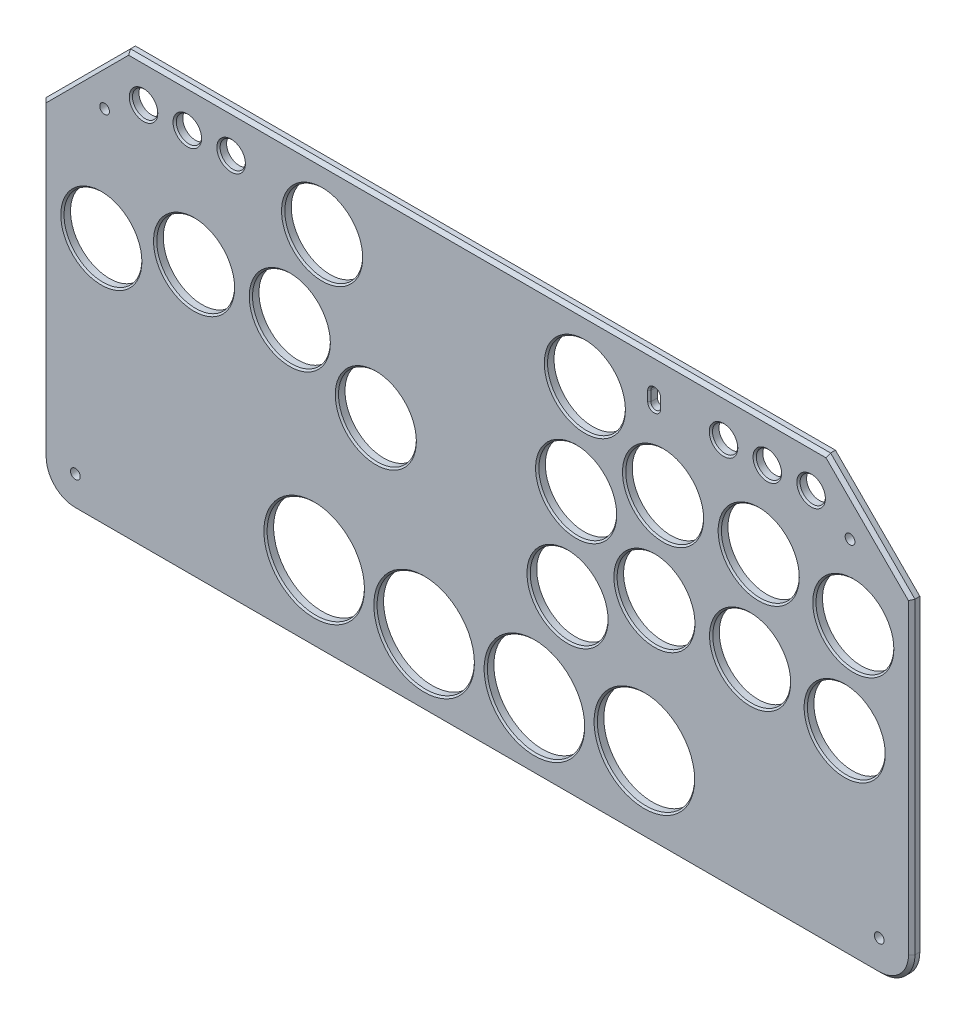
SolidWorks part; units mm, degrees
ref_plane "Front Plane" through (0, 0, 0) normal (0, 0, 1) x (1, 0, 0)
ref_plane "Top Plane" through (0, 0, 0) normal (0, 1, 0) x (1, 0, 0)
ref_plane "Right Plane" through (0, 0, 0) normal (1, 0, 0) x (0, 0, -1)
sketch "Sketch1" plane through (0, 0, 0) normal (0, 0, 1) x (1, 0, 0)
  line L0 (157.8919, 26.2701) -> (191.7747, 29.0915)
  line L1 (157.8919, 26.2701) -> (191.7747, 26.2701)
  line L2 (157.8919, 26.2701) -> (157.8919, 29.0915)
  line L3 (157.8919, 29.0915) -> (191.7747, 29.0915)
  line L4 (191.7747, 26.2701) -> (191.7747, 29.0915)
  line L5 (123.8919, 26.2701) -> (90.0092, 26.2701)
  line L6 (123.8919, 26.2701) -> (123.8919, 29.0915)
  line L7 (123.8919, 29.0915) -> (90.0092, 29.0915)
  line L8 (90.0092, 26.2701) -> (90.0092, 29.0915)
  line L9 (90.0092, 29.0915) -> (123.8919, 26.2701)
  line L10 (168.0919, 58.3601) -> (194.8735, 70.7292)
  line L11 (168.0919, 58.3601) -> (194.8735, 58.3601)
  line L12 (168.0919, 58.3601) -> (168.0919, 70.7292)
  line L13 (168.0919, 70.7292) -> (194.8735, 70.7292)
  line L14 (194.8735, 58.3601) -> (194.8735, 70.7292)
  line L15 (194.8735, 70.7292) -> (224.3587, 70.7292)
  line L16 (194.8735, 70.7292) -> (194.8735, 69.7923)
  line L17 (194.8735, 69.7923) -> (224.3587, 69.7923)
  line L18 (224.3587, 70.7292) -> (224.3587, 69.7923)
  line L19 (224.3587, 69.7923) -> (253.5106, 69.7923)
  line L20 (224.3587, 69.7923) -> (224.3587, 65.2742)
  line L21 (224.3587, 65.2742) -> (253.5106, 65.2742)
  line L22 (253.5106, 69.7923) -> (253.5106, 65.2742)
  line L23 (224.3587, 69.7923) -> (194.8735, 70.7292)
  line L24 (253.5106, 65.2742) -> (224.3587, 69.7923)
  line L25 (170.7502, 87.7401) -> (168.0919, 58.3601)
  line L26 (168.0919, 58.3601) -> (170.7502, 58.3601)
  line L27 (168.0919, 58.3601) -> (168.0919, 87.7401)
  line L28 (168.0919, 87.7401) -> (170.7502, 87.7401)
  line L29 (170.7502, 58.3601) -> (170.7502, 87.7401)
  line L30 (52.9966, 89.4705) -> (24.4119, 82.1791)
  line L31 (24.4119, 82.1791) -> (52.9966, 82.1791)
  line L32 (24.4119, 82.1791) -> (24.4119, 89.4705)
  line L33 (24.4119, 89.4705) -> (52.9966, 89.4705)
  line L34 (52.9966, 82.1791) -> (52.9966, 89.4705)
  line L35 (82.4966, 89.4705) -> (109.0019, 89.4705)
  line L36 (82.4966, 89.4705) -> (82.4966, 76.5201)
  line L37 (82.4966, 76.5201) -> (109.0019, 76.5201)
  line L38 (109.0019, 89.4705) -> (109.0019, 76.5201)
  line L39 (92.4554, 117.2387) -> (82.4966, 117.2387)
  line L40 (92.4554, 117.2387) -> (92.4554, 89.4705)
  line L41 (92.4554, 89.4705) -> (82.4966, 89.4705)
  line L42 (82.4966, 117.2387) -> (82.4966, 89.4705)
  line L43 (92.4554, 117.2387) -> (82.4966, 89.4705)
  line L44 (109.0019, 76.5201) -> (82.4966, 89.4705)
  circle A0 centre (123.8919, 26.2701) radius 14.25
  circle A1 centre (157.8919, 26.2701) radius 14.25
  circle A2 centre (90.0092, 29.0915) radius 14.25
  circle A3 centre (191.7747, 29.0915) radius 14.25
  circle A4 centre (82.4966, 89.4705) radius 11.25
  circle A5 centre (92.4554, 117.2387) radius 11.25
  circle A6 centre (52.9966, 89.4705) radius 11.25
  circle A7 centre (109.0019, 76.5201) radius 11.25
  circle A8 centre (24.4119, 82.1791) radius 11.25
  circle A9 centre (170.7502, 87.7401) radius 11.25
  circle A10 centre (168.0919, 58.3601) radius 11.25
  circle A11 centre (197.5318, 100.1092) radius 11.25
  circle A12 centre (194.8735, 70.7292) radius 11.25
  circle A13 centre (227.0169, 99.1723) radius 11.25
  circle A14 centre (224.3587, 69.7923) radius 11.25
  circle A15 centre (256.1689, 94.6541) radius 11.25
  circle A16 centre (253.5106, 65.2742) radius 11.25
  circle A17 centre (24.4119, 82.1791) radius 12
  circle A18 centre (52.9966, 89.4705) radius 12
  circle A19 centre (92.4554, 117.2387) radius 12
  circle A20 centre (82.4966, 89.4705) radius 12
  circle A21 centre (109.0019, 76.5201) radius 12
  circle A22 centre (168.0919, 58.3601) radius 12
  circle A23 centre (194.8735, 70.7292) radius 12
  circle A24 centre (224.3587, 69.7923) radius 12
  circle A25 centre (253.5106, 65.2742) radius 12
  circle A26 centre (256.1689, 94.6541) radius 12
  circle A27 centre (227.0169, 99.1723) radius 12
  circle A28 centre (197.5318, 100.1092) radius 12
  circle A29 centre (170.7502, 87.7401) radius 12
  circle A30 centre (191.7747, 29.0915) radius 15
  circle A31 centre (157.8919, 26.2701) radius 15
  circle A32 centre (123.8919, 26.2701) radius 15
  circle A33 centre (90.0092, 29.0915) radius 15
  circle A34 centre (173.429, 117.1182) radius 11.25
  circle A35 centre (173.429, 117.1182) radius 12
  dimension "D1" = 28.5
  dimension "D2" = 22.5
  dimension "D3" = 0.75
  dimension "D4" = 0.75
  dimension "D34" = 34
  dimension "D5" = 29.5
  dimension "D6" = 29.5
  dimension "D7" = 29.5
  dimension "D8" = 29.5
  dimension "D9" = 29.5
  dimension "D10" = 29.5
  dimension "D11" = 29.5
  dimension "D12" = 29.5
  dimension "D13" = 29.5
  dimension "D14" = 29.5
  dimension "D15" = 29.5
  dimension "D16" = 29.5
  dimension "D17" = 29.5
  dimension "D18" = 29.5
  dimension "D19" = 34
  dimension "D20" = 34
  dimension "D21" = 32.09
  dimension "D22" = 10.2
  dimension "D23" = 4.76
  dimension "D24" = 4.76
  dimension "D25" = 24.79
  dimension "D26" = 1.82
  dimension "D27" = 8.81
  dimension "D28" = 84.83
  dimension "D29" = 75.69
  dimension "D30" = 70.27
  dimension "D31" = 26.04
  dimension "D32" = 14.89
  dimension "D33" = 50.25
  dimension "D35" = 29.5
  dimension "D36" = 29.5
sketch "Sketch4" plane through (-30.2083, 20.075, 0) normal (0, 0, 1) x (0.9781, -0.2079, 0)
  line L0 (86.1706, 94.1917) -> (105.2206, 75.1417)
  line L1 (67.1206, 94.1917) -> (86.1706, 94.1917)
  line L2 (67.1206, 94.1917) -> (67.1206, 75.1417)
  line L3 (67.1206, 75.1417) -> (86.1706, 75.1417)
  line L4 (86.1706, 94.1917) -> (86.1706, 75.1417)
  line L5 (86.1706, 94.1917) -> (105.2206, 94.1917)
  line L6 (86.1706, 94.1917) -> (86.1706, 75.1417)
  line L7 (86.1706, 75.1417) -> (105.2206, 75.1417)
  line L8 (105.2206, 94.1917) -> (105.2206, 75.1417)
  line L9 (105.2206, 94.1917) -> (124.2706, 94.1917)
  line L10 (105.2206, 94.1917) -> (105.2206, 75.1417)
  line L11 (105.2206, 75.1417) -> (124.2706, 75.1417)
  line L12 (124.2706, 94.1917) -> (124.2706, 75.1417)
  line L13 (86.1706, 94.1917) -> (105.2206, 94.1917)
  line L14 (86.1706, 94.1917) -> (86.1706, 113.2417)
  line L15 (86.1706, 113.2417) -> (105.2206, 113.2417)
  line L16 (105.2206, 94.1917) -> (105.2206, 113.2417)
  line L17 (66.9585, 85.1784) -> (124.4326, 84.1551)
  point P14 (95.6956, 84.6667)
  point P15 (95.6956, 84.6667)
  dimension "D1" = 19.05
sketch "Sketch9" plane through (0, 0, 0) normal (0, 0, 1) x (1, 0, 0)
  line L1 (17.3619, 89.2291) -> (31.4619, 89.2291)
  line L2 (17.3619, 89.2291) -> (17.3619, 75.1291)
  line L3 (17.3619, 75.1291) -> (31.4619, 75.1291)
  line L4 (31.4619, 89.2291) -> (31.4619, 75.1291)
  line L5 (45.9466, 96.5205) -> (60.0466, 96.5205)
  line L6 (45.9466, 96.5205) -> (45.9466, 82.4205)
  line L7 (45.9466, 82.4205) -> (60.0466, 82.4205)
  line L8 (60.0466, 96.5205) -> (60.0466, 82.4205)
  line L9 (75.4466, 96.5205) -> (89.5466, 96.5205)
  line L10 (75.4466, 96.5205) -> (75.4466, 82.4205)
  line L11 (75.4466, 82.4205) -> (89.5466, 82.4205)
  line L12 (89.5466, 96.5205) -> (89.5466, 82.4205)
  line L13 (101.9519, 83.5701) -> (116.0519, 83.5701)
  line L14 (101.9519, 83.5701) -> (101.9519, 69.4701)
  line L15 (101.9519, 69.4701) -> (116.0519, 69.4701)
  line L16 (116.0519, 83.5701) -> (116.0519, 69.4701)
  line L17 (85.4054, 124.2887) -> (99.5054, 124.2887)
  line L18 (85.4054, 124.2887) -> (85.4054, 110.1887)
  line L19 (85.4054, 110.1887) -> (99.5054, 110.1887)
  line L20 (99.5054, 124.2887) -> (99.5054, 110.1887)
  line L21 (82.9592, 36.1415) -> (97.0592, 36.1415)
  line L22 (82.9592, 36.1415) -> (82.9592, 22.0415)
  line L23 (82.9592, 22.0415) -> (97.0592, 22.0415)
  line L24 (97.0592, 36.1415) -> (97.0592, 22.0415)
  line L25 (116.8419, 33.3201) -> (130.9419, 33.3201)
  line L26 (116.8419, 33.3201) -> (116.8419, 19.2201)
  line L27 (116.8419, 19.2201) -> (130.9419, 19.2201)
  line L28 (130.9419, 33.3201) -> (130.9419, 19.2201)
  line L29 (150.8419, 33.3201) -> (164.9419, 33.3201)
  line L30 (150.8419, 33.3201) -> (150.8419, 19.2201)
  line L31 (150.8419, 19.2201) -> (164.9419, 19.2201)
  line L32 (164.9419, 33.3201) -> (164.9419, 19.2201)
  line L33 (184.7247, 36.1415) -> (198.8247, 36.1415)
  line L34 (184.7247, 36.1415) -> (184.7247, 22.0415)
  line L35 (184.7247, 22.0415) -> (198.8247, 22.0415)
  line L36 (198.8247, 36.1415) -> (198.8247, 22.0415)
  line L37 (260.5606, 58.2242) -> (246.4606, 58.2242)
  line L38 (260.5606, 58.2242) -> (260.5606, 72.3242)
  line L39 (260.5606, 72.3242) -> (246.4606, 72.3242)
  line L40 (246.4606, 58.2242) -> (246.4606, 72.3242)
  line L41 (217.3087, 76.8423) -> (231.4087, 76.8423)
  line L42 (217.3087, 76.8423) -> (217.3087, 62.7423)
  line L43 (217.3087, 62.7423) -> (231.4087, 62.7423)
  line L44 (231.4087, 76.8423) -> (231.4087, 62.7423)
  line L45 (187.8235, 77.7792) -> (201.9235, 77.7792)
  line L46 (187.8235, 77.7792) -> (187.8235, 63.6792)
  line L47 (187.8235, 63.6792) -> (201.9235, 63.6792)
  line L48 (201.9235, 77.7792) -> (201.9235, 63.6792)
  line L49 (161.0419, 65.4101) -> (175.1419, 65.4101)
  line L50 (161.0419, 65.4101) -> (161.0419, 51.3101)
  line L51 (161.0419, 51.3101) -> (175.1419, 51.3101)
  line L52 (175.1419, 65.4101) -> (175.1419, 51.3101)
  line L53 (163.7002, 94.7901) -> (177.8002, 94.7901)
  line L54 (163.7002, 94.7901) -> (163.7002, 80.6901)
  line L55 (163.7002, 80.6901) -> (177.8002, 80.6901)
  line L56 (177.8002, 94.7901) -> (177.8002, 80.6901)
  line L57 (190.4818, 107.1592) -> (204.5818, 107.1592)
  line L58 (190.4818, 107.1592) -> (190.4818, 93.0592)
  line L59 (190.4818, 93.0592) -> (204.5818, 93.0592)
  line L60 (204.5818, 107.1592) -> (204.5818, 93.0592)
  line L61 (219.9669, 106.2223) -> (234.0669, 106.2223)
  line L62 (219.9669, 106.2223) -> (219.9669, 92.1223)
  line L63 (219.9669, 92.1223) -> (234.0669, 92.1223)
  line L64 (234.0669, 106.2223) -> (234.0669, 92.1223)
  line L65 (249.1189, 101.7041) -> (263.2189, 101.7041)
  line L66 (249.1189, 101.7041) -> (249.1189, 87.6041)
  line L67 (249.1189, 87.6041) -> (263.2189, 87.6041)
  line L68 (263.2189, 101.7041) -> (263.2189, 87.6041)
  line L69 (166.379, 124.1682) -> (180.479, 124.1682)
  line L70 (166.379, 124.1682) -> (166.379, 110.0682)
  line L71 (166.379, 110.0682) -> (180.479, 110.0682)
  line L72 (180.479, 124.1682) -> (180.479, 110.0682)
  point P72 (24.4119, 89.2291)
  point P74 (52.9966, 96.5205)
  point P76 (82.4966, 96.5205)
  point P78 (92.4554, 124.2887)
  point P80 (109.0019, 83.5701)
  point P82 (90.0092, 36.1415)
  point P84 (123.8919, 33.3201)
  point P86 (157.8919, 33.3201)
  point P88 (191.7747, 36.1415)
  point P90 (168.0919, 65.4101)
  point P92 (170.7502, 94.7901)
  point P94 (173.429, 124.1682)
  point P96 (197.5318, 107.1592)
  point P98 (227.0169, 106.2223)
  point P100 (256.1689, 101.7041)
  point P102 (194.8735, 77.7792)
  point P104 (224.3587, 76.8423)
  point P106 (253.5106, 72.3242)
  point P108 (17.3619, 82.1791)
  point P109 (45.9466, 89.4705)
  point P110 (75.4466, 89.4705)
  point P111 (101.9519, 76.5201)
  point P112 (85.4054, 117.2387)
  point P113 (82.9592, 29.0915)
  point P114 (116.8419, 26.2701)
  point P115 (150.8419, 26.2701)
  point P116 (184.7247, 29.0915)
  point P118 (161.0419, 58.3601)
  point P119 (187.8235, 70.7292)
  point P120 (217.3087, 69.7923)
  point P121 (246.4606, 65.2742)
  point P122 (163.7002, 87.7401)
  point P123 (190.4818, 100.1092)
  point P124 (219.9669, 99.1723)
  point P125 (249.1189, 94.6541)
  point P126 (166.379, 117.1182)
  dimension "D1" = 14.1
sketch "Sketch10" plane through (-22.0981, 19.3454, 0) normal (0, 0, 1) x (0.9781, -0.2079, 0)
  line L1 (61.5108, 90.7441) -> (75.6108, 90.7441)
  line L2 (61.5108, 90.7441) -> (61.5108, 76.6441)
  line L3 (61.5108, 76.6441) -> (75.6108, 76.6441)
  line L4 (75.6108, 90.7441) -> (75.6108, 76.6441)
  line L5 (80.5608, 90.7441) -> (94.6608, 90.7441)
  line L6 (80.5608, 90.7441) -> (80.5608, 76.6441)
  line L7 (80.5608, 76.6441) -> (94.6608, 76.6441)
  line L8 (94.6608, 90.7441) -> (94.6608, 76.6441)
  line L9 (99.6108, 90.7441) -> (113.7108, 90.7441)
  line L10 (99.6108, 90.7441) -> (99.6108, 76.6441)
  line L11 (99.6108, 76.6441) -> (113.7108, 76.6441)
  line L12 (113.7108, 90.7441) -> (113.7108, 76.6441)
  line L13 (80.5608, 109.7941) -> (94.6608, 109.7941)
  line L14 (80.5608, 109.7941) -> (80.5608, 95.6941)
  line L15 (80.5608, 95.6941) -> (94.6608, 95.6941)
  line L16 (94.6608, 109.7941) -> (94.6608, 95.6941)
  line L17 (50.5121, 89.6359) -> (53.4436, 75.8441) construction
  line L18 (59.0358, 93.2191) -> (78.0858, 93.2191) construction
  line L19 (78.0858, 112.2691) -> (97.1358, 112.2691) construction
  line L20 (97.1358, 93.2191) -> (116.1858, 93.2191) construction
  line L21 (78.0858, 93.2191) -> (78.0858, 112.2691) construction
  line L23 (59.0358, 93.2191) -> (59.0358, 74.1691) construction
  point P16 (75.6108, 83.6941)
  point P17 (94.6608, 83.6941)
  point P18 (113.7108, 83.6941)
  point P19 (87.6108, 90.7441)
  point P20 (87.6108, 109.7941)
  point P23 (68.5608, 90.7441)
  point P26 (68.5608, 93.2191)
  point P29 (87.6108, 112.2691)
  point P30 (106.6608, 90.7441)
  point P33 (106.6608, 93.2191)
  point P34 (80.5608, 102.7441)
  point P37 (78.0858, 102.7441)
  point P42 (59.0358, 83.6941)
  point P43 (61.5108, 83.6941)
sketch "Sketch14" plane through (0, 0, 0) normal (0, 0, 1) x (1, 0, 0)
  line L0 (165.1144, 80.6901) -> (163.7002, 82.1043)
  line L1 (163.7002, 93.3758) -> (165.1144, 94.7901)
  line L2 (177.8002, 93.3758) -> (176.386, 94.7901)
  line L3 (179.0648, 110.0682) -> (180.479, 111.4824)
  line L4 (166.379, 111.4824) -> (167.7932, 110.0682)
  line L5 (166.379, 122.754) -> (167.7932, 124.1682)
  line L6 (179.0648, 124.1682) -> (180.479, 122.754)
  line L7 (203.1676, 93.0592) -> (204.5818, 94.4734)
  line L8 (17.3619, 89.2291) -> (17.3619, 75.1291) construction
  line L9 (17.3619, 89.2291) -> (31.4619, 89.2291) construction
  line L10 (17.3619, 87.8149) -> (18.7761, 89.2291)
  line L11 (17.3619, 75.1291) -> (31.4619, 75.1291) construction
  line L12 (31.4619, 89.2291) -> (31.4619, 75.1291) construction
  line L13 (45.9466, 96.5205) -> (60.0466, 96.5205) construction
  line L14 (60.0466, 96.5205) -> (60.0466, 82.4205) construction
  line L15 (45.9466, 96.5205) -> (45.9466, 82.4205) construction
  line L16 (45.9466, 82.4205) -> (60.0466, 82.4205) construction
  line L17 (85.4054, 124.2887) -> (85.4054, 110.1887) construction
  line L18 (85.4054, 124.2887) -> (99.5054, 124.2887) construction
  line L19 (99.5054, 124.2887) -> (99.5054, 110.1887) construction
  line L20 (85.4054, 110.1887) -> (99.5054, 110.1887) construction
  line L21 (101.9519, 83.5701) -> (101.9519, 69.4701) construction
  line L22 (101.9519, 83.5701) -> (116.0519, 83.5701) construction
  line L23 (116.0519, 83.5701) -> (116.0519, 69.4701) construction
  line L24 (101.9519, 69.4701) -> (116.0519, 69.4701) construction
  line L25 (91.2712, 73.6044) -> (105.0631, 70.6729) construction
  line L26 (107.9947, 84.4647) -> (105.0631, 70.6729) construction
  line L27 (94.2028, 87.3963) -> (107.9947, 84.4647) construction
  line L28 (94.2028, 87.3963) -> (91.2712, 73.6044) construction
  line L29 (72.6375, 77.5651) -> (86.4294, 74.6336) construction
  line L30 (89.361, 88.4255) -> (86.4294, 74.6336) construction
  line L31 (75.5691, 91.357) -> (89.361, 88.4255) construction
  line L32 (75.5691, 91.357) -> (72.6375, 77.5651) construction
  line L33 (56.9354, 95.3177) -> (54.0038, 81.5259) construction
  line L34 (56.9354, 95.3177) -> (70.7273, 92.3862) construction
  line L35 (70.7273, 92.3862) -> (67.7957, 78.5943) construction
  line L36 (54.0038, 81.5259) -> (67.7957, 78.5943) construction
  line L37 (76.5983, 96.1988) -> (90.3901, 93.2673) construction
  line L38 (93.3217, 107.0592) -> (90.3901, 93.2673) construction
  line L39 (79.5298, 109.9907) -> (76.5983, 96.1988) construction
  line L40 (79.5298, 109.9907) -> (93.3217, 107.0592) construction
  line L41 (82.9592, 36.1415) -> (82.9592, 22.0415) construction
  line L42 (82.9592, 36.1415) -> (97.0592, 36.1415) construction
  line L43 (82.9592, 22.0415) -> (97.0592, 22.0415) construction
  line L44 (97.0592, 36.1415) -> (97.0592, 22.0415) construction
  line L45 (116.8419, 33.3201) -> (116.8419, 19.2201) construction
  line L46 (116.8419, 33.3201) -> (130.9419, 33.3201) construction
  line L47 (116.8419, 19.2201) -> (130.9419, 19.2201) construction
  line L48 (130.9419, 33.3201) -> (130.9419, 19.2201) construction
  line L49 (150.8419, 33.3201) -> (150.8419, 19.2201) construction
  line L50 (150.8419, 33.3201) -> (164.9419, 33.3201) construction
  line L51 (164.9419, 33.3201) -> (164.9419, 19.2201) construction
  line L52 (150.8419, 19.2201) -> (164.9419, 19.2201) construction
  line L53 (184.7247, 36.1415) -> (184.7247, 22.0415) construction
  line L54 (184.7247, 22.0415) -> (198.8247, 22.0415) construction
  line L55 (198.8247, 36.1415) -> (198.8247, 22.0415) construction
  line L56 (184.7247, 36.1415) -> (198.8247, 36.1415) construction
  line L57 (161.0419, 65.4101) -> (175.1419, 65.4101) construction
  line L58 (175.1419, 65.4101) -> (175.1419, 51.3101) construction
  line L59 (161.0419, 51.3101) -> (175.1419, 51.3101) construction
  line L60 (161.0419, 65.4101) -> (161.0419, 51.3101) construction
  line L61 (187.8235, 77.7792) -> (187.8235, 63.6792) construction
  line L62 (187.8235, 77.7792) -> (201.9235, 77.7792) construction
  line L63 (187.8235, 63.6792) -> (201.9235, 63.6792) construction
  line L64 (201.9235, 77.7792) -> (201.9235, 63.6792) construction
  line L65 (217.3087, 76.8423) -> (217.3087, 62.7423) construction
  line L66 (217.3087, 76.8423) -> (231.4087, 76.8423) construction
  line L67 (231.4087, 76.8423) -> (231.4087, 62.7423) construction
  line L68 (217.3087, 62.7423) -> (231.4087, 62.7423) construction
  line L69 (260.5606, 58.2242) -> (246.4606, 58.2242) construction
  line L70 (260.5606, 58.2242) -> (260.5606, 72.3242) construction
  line L71 (246.4606, 58.2242) -> (246.4606, 72.3242) construction
  line L72 (260.5606, 72.3242) -> (246.4606, 72.3242) construction
  line L73 (249.1189, 101.7041) -> (263.2189, 101.7041) construction
  line L74 (263.2189, 101.7041) -> (263.2189, 87.6041) construction
  line L75 (249.1189, 87.6041) -> (263.2189, 87.6041) construction
  line L76 (249.1189, 101.7041) -> (249.1189, 87.6041) construction
  line L77 (219.9669, 106.2223) -> (219.9669, 92.1223) construction
  line L78 (219.9669, 106.2223) -> (234.0669, 106.2223) construction
  line L79 (234.0669, 106.2223) -> (234.0669, 92.1223) construction
  line L80 (219.9669, 92.1223) -> (234.0669, 92.1223) construction
  line L81 (190.4818, 107.1592) -> (204.5818, 107.1592) construction
  line L82 (204.5818, 107.1592) -> (204.5818, 93.0592) construction
  line L83 (190.4818, 93.0592) -> (204.5818, 93.0592) construction
  line L84 (190.4818, 107.1592) -> (190.4818, 93.0592) construction
  line L85 (163.7002, 94.7901) -> (177.8002, 94.7901) construction
  line L86 (177.8002, 94.7901) -> (177.8002, 80.6901) construction
  line L87 (163.7002, 80.6901) -> (177.8002, 80.6901) construction
  line L88 (163.7002, 94.7901) -> (163.7002, 80.6901) construction
  line L89 (180.479, 124.1682) -> (180.479, 110.0682) construction
  line L90 (166.379, 110.0682) -> (180.479, 110.0682) construction
  line L91 (166.379, 124.1682) -> (166.379, 110.0682) construction
  line L92 (166.379, 124.1682) -> (180.479, 124.1682) construction
  line L93 (17.3619, 76.5433) -> (18.7761, 75.1291)
  line L94 (30.0477, 75.1291) -> (31.4619, 76.5433)
  line L95 (31.4619, 87.8149) -> (30.0477, 89.2291)
  line L96 (45.9466, 95.1063) -> (47.3608, 96.5205)
  line L97 (45.9466, 83.8347) -> (47.3608, 82.4205)
  line L98 (54.2979, 82.9092) -> (55.3871, 81.2318)
  line L99 (58.6323, 82.4205) -> (60.0466, 83.8347)
  line L100 (56.6413, 93.9344) -> (58.3187, 95.0237)
  line L101 (58.6323, 96.5205) -> (60.0466, 95.1063)
  line L102 (69.3439, 92.6802) -> (70.4332, 91.0029)
  line L103 (68.0897, 79.9776) -> (66.4124, 78.8883)
  line L104 (75.2751, 89.9737) -> (76.9524, 91.063)
  line L105 (72.9316, 78.9484) -> (74.0208, 77.2711)
  line L106 (85.0461, 74.9276) -> (86.7234, 76.0169)
  line L107 (89.0669, 87.0421) -> (87.9777, 88.7195)
  line L108 (89.0068, 93.5613) -> (90.6842, 94.6506)
  line L109 (76.8923, 97.5822) -> (77.9816, 95.9048)
  line L110 (91.9384, 107.3532) -> (93.0277, 105.6759)
  line L111 (79.2358, 108.6074) -> (80.9131, 109.6967)
  line L112 (85.4054, 111.6029) -> (86.8196, 110.1887)
  line L113 (98.0912, 110.1887) -> (99.5054, 111.6029)
  line L114 (98.0912, 124.2887) -> (99.5054, 122.8745)
  line L115 (85.4054, 122.8745) -> (86.8196, 124.2887)
  line L116 (93.9088, 86.013) -> (95.5861, 87.1023)
  line L117 (91.5653, 74.9877) -> (92.6546, 73.3104)
  line L118 (103.6798, 70.9669) -> (105.3572, 72.0562)
  line L119 (106.6114, 84.7588) -> (107.7006, 83.0814)
  line L120 (101.9519, 82.1559) -> (103.3662, 83.5701)
  line L121 (101.9519, 70.8843) -> (103.3662, 69.4701)
  line L122 (114.6377, 69.4701) -> (116.0519, 70.8843)
  line L123 (116.0519, 82.1559) -> (114.6377, 83.5701)
  line L124 (82.9592, 34.7272) -> (84.3734, 36.1415)
  line L125 (82.9592, 23.4557) -> (84.3734, 22.0415)
  line L126 (95.645, 22.0415) -> (97.0592, 23.4557)
  line L127 (97.0592, 34.7272) -> (95.645, 36.1415)
  line L128 (116.8419, 31.9059) -> (118.2562, 33.3201)
  line L129 (116.8419, 20.6343) -> (118.2562, 19.2201)
  line L130 (129.5277, 19.2201) -> (130.9419, 20.6343)
  line L131 (130.9419, 31.9059) -> (129.5277, 33.3201)
  line L132 (150.8419, 31.9059) -> (152.2562, 33.3201)
  line L133 (150.8419, 20.6343) -> (152.2562, 19.2201)
  line L134 (163.5277, 19.2201) -> (164.9419, 20.6343)
  line L135 (164.9419, 31.9059) -> (163.5277, 33.3201)
  line L136 (184.7247, 34.7272) -> (186.1389, 36.1415)
  line L137 (184.7247, 23.4557) -> (186.1389, 22.0415)
  line L138 (197.4105, 22.0415) -> (198.8247, 23.4557)
  line L139 (198.8247, 34.7272) -> (197.4105, 36.1415)
  line L140 (173.7277, 51.3101) -> (175.1419, 52.7243)
  line L141 (161.0419, 52.7243) -> (162.4562, 51.3101)
  line L142 (161.0419, 63.9959) -> (162.4562, 65.4101)
  line L143 (173.7277, 65.4101) -> (175.1419, 63.9959)
  line L144 (187.8235, 65.0934) -> (189.2378, 63.6792)
  line L145 (200.5093, 63.6792) -> (201.9235, 65.0934)
  line L146 (200.5093, 77.7792) -> (201.9235, 76.365)
  line L147 (187.8235, 76.365) -> (189.2378, 77.7792)
  line L148 (176.386, 80.6901) -> (177.8002, 82.1043)
  line L149 (204.5818, 105.745) -> (203.1676, 107.1592)
  line L150 (191.896, 107.1592) -> (190.4818, 105.745)
  line L151 (190.4818, 94.4734) -> (191.896, 93.0592)
  line L152 (219.9669, 104.8081) -> (221.3812, 106.2223)
  line L153 (232.6527, 106.2223) -> (234.0669, 104.8081)
  line L154 (234.0669, 93.5365) -> (232.6527, 92.1223)
  line L155 (219.9669, 93.5365) -> (221.3812, 92.1223)
  line L156 (229.9944, 76.8423) -> (231.4087, 75.4281)
  line L157 (217.3087, 75.4281) -> (218.7229, 76.8423)
  line L158 (217.3087, 64.1565) -> (218.7229, 62.7423)
  line L159 (229.9944, 62.7423) -> (231.4087, 64.1565)
  line L160 (259.1464, 72.3242) -> (260.5606, 70.9099)
  line L161 (246.4606, 70.9099) -> (247.8748, 72.3242)
  line L162 (259.1464, 58.2242) -> (260.5606, 59.6384)
  line L163 (247.8748, 58.2242) -> (246.4606, 59.6384)
  line L164 (261.8047, 87.6041) -> (263.2189, 89.0183)
  line L165 (249.1189, 89.0183) -> (250.5331, 87.6041)
  line L166 (249.1189, 100.2899) -> (250.5331, 101.7041)
  line L167 (261.8047, 101.7041) -> (263.2189, 100.2899)
  line L168 (75.4466, 96.5205) -> (75.4466, 82.4205) construction
  line L169 (75.4466, 96.5205) -> (89.5466, 96.5205) construction
  line L170 (89.5466, 96.5205) -> (89.5466, 82.4205) construction
  line L171 (75.4466, 82.4205) -> (89.5466, 82.4205) construction
  line L172 (76.8608, 96.5205) -> (75.4466, 95.1063)
  line L173 (88.1323, 96.5205) -> (89.5466, 95.1063)
  line L174 (89.5466, 83.8347) -> (88.1323, 82.4205)
  line L175 (75.4466, 83.8347) -> (76.8608, 82.4205)
  arc A0 (17.3619, 87.8149) -> (18.7761, 89.2291) centre (18.069, 88.522) cw
  arc A1 (18.7761, 75.1291) -> (17.3619, 76.5433) centre (18.069, 75.8362) cw
  arc A2 (31.4619, 76.5433) -> (30.0477, 75.1291) centre (30.7548, 75.8362) cw
  arc A3 (30.0477, 89.2291) -> (31.4619, 87.8149) centre (30.7548, 88.522) cw
  arc A4 (58.6323, 96.5205) -> (60.0466, 95.1063) centre (59.3394, 95.8134) cw
  arc A5 (45.9466, 95.1063) -> (47.3608, 96.5205) centre (46.6537, 95.8134) cw
  arc A6 (47.3608, 82.4205) -> (45.9466, 83.8347) centre (46.6537, 83.1276) cw
  arc A7 (60.0466, 83.8347) -> (58.6323, 82.4205) centre (59.3394, 83.1276) cw
  arc A8 (85.4054, 122.8745) -> (86.8196, 124.2887) centre (86.1125, 123.5816) cw
  arc A9 (98.0912, 124.2887) -> (99.5054, 122.8745) centre (98.7983, 123.5816) cw
  arc A10 (99.5054, 111.6029) -> (98.0912, 110.1887) centre (98.7983, 110.8958) cw
  arc A11 (85.4054, 111.6029) -> (86.8196, 110.1887) centre (86.1125, 110.8958) ccw
  arc A12 (101.9519, 82.1559) -> (103.3662, 83.5701) centre (102.6591, 82.863) cw
  arc A13 (114.6377, 83.5701) -> (116.0519, 82.1559) centre (115.3448, 82.863) cw
  arc A14 (116.0519, 70.8843) -> (114.6377, 69.4701) centre (115.3448, 70.1772) cw
  arc A15 (101.9519, 70.8843) -> (103.3662, 69.4701) centre (102.6591, 70.1772) ccw
  arc A16 (103.6798, 70.9669) -> (105.3572, 72.0562) centre (104.5185, 71.5115) ccw
  arc A17 (106.6114, 84.7588) -> (107.7006, 83.0814) centre (107.156, 83.9201) cw
  arc A18 (93.9088, 86.013) -> (95.5861, 87.1023) centre (94.7474, 86.5576) cw
  arc A19 (91.5653, 74.9877) -> (92.6546, 73.3104) centre (92.1099, 74.1491) ccw
  arc A20 (85.0461, 74.9276) -> (86.7234, 76.0169) centre (85.8848, 75.4722) ccw
  arc A21 (87.9777, 88.7195) -> (89.0669, 87.0421) centre (88.5223, 87.8808) cw
  arc A22 (75.2751, 89.9737) -> (76.9524, 91.063) centre (76.1137, 90.5183) cw
  arc A23 (72.9316, 78.9484) -> (74.0208, 77.2711) centre (73.4762, 78.1098) ccw
  arc A24 (56.6413, 93.9344) -> (58.3187, 95.0237) centre (57.48, 94.4791) cw
  arc A25 (69.3439, 92.6802) -> (70.4332, 91.0029) centre (69.8886, 91.8415) cw
  arc A26 (68.0897, 79.9776) -> (66.4124, 78.8883) centre (67.2511, 79.433) cw
  arc A27 (54.2979, 82.9092) -> (55.3871, 81.2318) centre (54.8425, 82.0705) ccw
  arc A28 (89.0068, 93.5613) -> (90.6842, 94.6506) centre (89.8455, 94.106) ccw
  arc A29 (76.8923, 97.5822) -> (77.9816, 95.9048) centre (77.4369, 96.7435) ccw
  arc A30 (79.2358, 108.6074) -> (80.9131, 109.6967) centre (80.0744, 109.1521) cw
  arc A31 (91.9384, 107.3532) -> (93.0277, 105.6759) centre (92.483, 106.5145) cw
  arc A32 (82.9592, 34.7272) -> (84.3734, 36.1415) centre (83.6663, 35.4344) cw
  arc A33 (82.9592, 23.4557) -> (84.3734, 22.0415) centre (83.6663, 22.7486) ccw
  arc A34 (95.645, 22.0415) -> (97.0592, 23.4557) centre (96.3521, 22.7486) ccw
  arc A35 (95.645, 36.1415) -> (97.0592, 34.7272) centre (96.3521, 35.4344) cw
  arc A36 (116.8419, 31.9059) -> (118.2562, 33.3201) centre (117.5491, 32.613) cw
  arc A37 (116.8419, 20.6343) -> (118.2562, 19.2201) centre (117.5491, 19.9272) ccw
  arc A38 (129.5277, 19.2201) -> (130.9419, 20.6343) centre (130.2348, 19.9272) ccw
  arc A39 (129.5277, 33.3201) -> (130.9419, 31.9059) centre (130.2348, 32.613) cw
  arc A40 (150.8419, 31.9059) -> (152.2562, 33.3201) centre (151.5491, 32.613) cw
  arc A41 (163.5277, 33.3201) -> (164.9419, 31.9059) centre (164.2348, 32.613) cw
  arc A42 (164.9419, 20.6343) -> (163.5277, 19.2201) centre (164.2348, 19.9272) cw
  arc A43 (150.8419, 20.6343) -> (152.2562, 19.2201) centre (151.5491, 19.9272) ccw
  arc A44 (184.7247, 23.4557) -> (186.1389, 22.0415) centre (185.4318, 22.7486) ccw
  arc A45 (197.4105, 22.0415) -> (198.8247, 23.4557) centre (198.1176, 22.7486) ccw
  arc A46 (197.4105, 36.1415) -> (198.8247, 34.7272) centre (198.1176, 35.4344) cw
  arc A47 (184.7247, 34.7272) -> (186.1389, 36.1415) centre (185.4318, 35.4344) cw
  arc A48 (173.7277, 65.4101) -> (175.1419, 63.9959) centre (174.4348, 64.703) cw
  arc A49 (175.1419, 52.7243) -> (173.7277, 51.3101) centre (174.4348, 52.0172) cw
  arc A50 (161.0419, 52.7243) -> (162.4562, 51.3101) centre (161.7491, 52.0172) ccw
  arc A51 (161.0419, 63.9959) -> (162.4562, 65.4101) centre (161.7491, 64.703) cw
  arc A52 (187.8235, 76.365) -> (189.2378, 77.7792) centre (188.5306, 77.0721) cw
  arc A53 (187.8235, 65.0934) -> (189.2378, 63.6792) centre (188.5306, 64.3863) ccw
  arc A54 (200.5093, 63.6792) -> (201.9235, 65.0934) centre (201.2164, 64.3863) ccw
  arc A55 (200.5093, 77.7792) -> (201.9235, 76.365) centre (201.2164, 77.0721) cw
  arc A56 (217.3087, 75.4281) -> (218.7229, 76.8423) centre (218.0158, 76.1352) cw
  arc A57 (229.9944, 76.8423) -> (231.4087, 75.4281) centre (230.7016, 76.1352) cw
  arc A58 (231.4087, 64.1565) -> (229.9944, 62.7423) centre (230.7016, 63.4494) cw
  arc A59 (217.3087, 64.1565) -> (218.7229, 62.7423) centre (218.0158, 63.4494) ccw
  arc A60 (259.1464, 58.2242) -> (260.5606, 59.6384) centre (259.8535, 58.9313) ccw
  arc A61 (246.4606, 59.6384) -> (247.8748, 58.2242) centre (247.1677, 58.9313) ccw
  arc A62 (246.4606, 70.9099) -> (247.8748, 72.3242) centre (247.1677, 71.617) cw
  arc A63 (259.1464, 72.3242) -> (260.5606, 70.9099) centre (259.8535, 71.617) cw
  arc A64 (261.8047, 101.7041) -> (263.2189, 100.2899) centre (262.5118, 100.997) cw
  arc A65 (263.2189, 89.0183) -> (261.8047, 87.6041) centre (262.5118, 88.3112) cw
  arc A66 (250.5331, 87.6041) -> (249.1189, 89.0183) centre (249.826, 88.3112) cw
  arc A67 (249.1189, 100.2899) -> (250.5331, 101.7041) centre (249.826, 100.997) cw
  arc A68 (219.9669, 104.8081) -> (221.3812, 106.2223) centre (220.674, 105.5152) cw
  arc A69 (232.6527, 106.2223) -> (234.0669, 104.8081) centre (233.3598, 105.5152) cw
  arc A70 (234.0669, 93.5365) -> (232.6527, 92.1223) centre (233.3598, 92.8294) cw
  arc A71 (221.3812, 92.1223) -> (219.9669, 93.5365) centre (220.674, 92.8294) cw
  arc A72 (203.1676, 107.1592) -> (204.5818, 105.745) centre (203.8747, 106.4521) cw
  arc A73 (204.5818, 94.4734) -> (203.1676, 93.0592) centre (203.8747, 93.7663) cw
  arc A74 (191.896, 93.0592) -> (190.4818, 94.4734) centre (191.1889, 93.7663) cw
  arc A75 (190.4818, 105.745) -> (191.896, 107.1592) centre (191.1889, 106.4521) cw
  arc A76 (176.386, 94.7901) -> (177.8002, 93.3758) centre (177.0931, 94.0829) cw
  arc A77 (177.8002, 82.1043) -> (176.386, 80.6901) centre (177.0931, 81.3972) cw
  arc A78 (165.1144, 80.6901) -> (163.7002, 82.1043) centre (164.4073, 81.3972) cw
  arc A79 (163.7002, 93.3758) -> (165.1144, 94.7901) centre (164.4073, 94.0829) cw
  arc A80 (180.479, 111.4824) -> (179.0648, 110.0682) centre (179.7719, 110.7753) cw
  arc A81 (167.7932, 110.0682) -> (166.379, 111.4824) centre (167.0861, 110.7753) cw
  arc A82 (179.0648, 124.1682) -> (180.479, 122.754) centre (179.7719, 123.4611) cw
  arc A83 (166.379, 122.754) -> (167.7932, 124.1682) centre (167.0861, 123.4611) cw
  arc A84 (75.4466, 95.1063) -> (76.8608, 96.5205) centre (76.1537, 95.8134) cw
  arc A85 (88.1323, 96.5205) -> (89.5466, 95.1063) centre (88.8394, 95.8134) cw
  arc A86 (89.5466, 83.8347) -> (88.1323, 82.4205) centre (88.8394, 83.1276) cw
  arc A87 (76.8608, 82.4205) -> (75.4466, 83.8347) centre (76.1537, 83.1276) cw
  dimension "D1" = 45
  dimension "D2" = 1
  dimension "D71" = 45
  dimension "D3" = 45
  dimension "D4" = 45
  dimension "D5" = 45
  dimension "D6" = 45
  dimension "D7" = 45
  dimension "D8" = 45
  dimension "D9" = 45
  dimension "D10" = 45
  dimension "D11" = 45
  dimension "D12" = 45
  dimension "D13" = 45
  dimension "D14" = 45
  dimension "D15" = 45
  dimension "D16" = 45
  dimension "D17" = 45
  dimension "D18" = 45
  dimension "D19" = 45
  dimension "D20" = 45
  dimension "D21" = 45
  dimension "D22" = 45
  dimension "D23" = 45
  dimension "D24" = 45
  dimension "D25" = 45
  dimension "D26" = 45
  dimension "D27" = 45
  dimension "D28" = 45
  dimension "D29" = 45
  dimension "D30" = 45
  dimension "D31" = 45
  dimension "D32" = 45
  dimension "D33" = 45
  dimension "D34" = 45
  dimension "D35" = 45
  dimension "D36" = 45
  dimension "D37" = 45
  dimension "D38" = 45
  dimension "D39" = 45
  dimension "D40" = 45
  dimension "D41" = 45
  dimension "D42" = 45
  dimension "D43" = 45
  dimension "D44" = 45
  dimension "D45" = 45
  dimension "D46" = 45
  dimension "D47" = 45
  dimension "D48" = 45
  dimension "D49" = 45
  dimension "D50" = 45
  dimension "D51" = 45
  dimension "D52" = 45
  dimension "D53" = 45
  dimension "D54" = 45
  dimension "D55" = 45
  dimension "D56" = 45
  dimension "D57" = 45
  dimension "D58" = 45
  dimension "D59" = 45
  dimension "D60" = 45
  dimension "D61" = 45
  dimension "D62" = 45
  dimension "D63" = 45
  dimension "D64" = 45
  dimension "D65" = 45
  dimension "D66" = 45
  dimension "D67" = 45
  dimension "D68" = 45
  dimension "D69" = 45
  dimension "D70" = 45
  dimension "D72" = 45
  dimension "D73" = 45
  dimension "D74" = 45
  dimension "D75" = 45
  dimension "D76" = 45
  dimension "D77" = 45
  dimension "D78" = 45
  dimension "D79" = 45
  dimension "D80" = 45
  dimension "D81" = 45
  dimension "D82" = 45
  dimension "D83" = 45
  dimension "D84" = 45
  dimension "D85" = 45
  dimension "D86" = 45
  dimension "D87" = 45
  dimension "D88" = 45
  dimension "D89" = 45
sketch "Sketch16" plane through (0, 0, 0) normal (0, 0, 1) x (1, 0, 0)
  line L0 (81.0092, 30.6915) -> (99.0092, 30.6915)
  line L5 (17.3619, 89.2291) -> (17.3619, 75.1291) construction
  line L6 (81.0092, 30.6915) -> (81.0092, 27.4915)
  line L7 (17.3619, 75.1291) -> (31.4619, 75.1291) construction
  line L8 (15.4119, 83.7791) -> (33.4119, 83.7791)
  line L9 (15.4119, 83.7791) -> (15.4119, 80.5791)
  line L10 (15.4119, 80.5791) -> (33.4119, 80.5791)
  line L11 (33.4119, 83.7791) -> (33.4119, 80.5791)
  line L12 (81.0092, 27.4915) -> (99.0092, 27.4915)
  line L13 (99.0092, 30.6915) -> (99.0092, 27.4915)
  line L14 (114.8919, 27.8701) -> (132.8919, 27.8701)
  line L15 (114.8919, 27.8701) -> (114.8919, 24.6701)
  line L16 (114.8919, 24.6701) -> (132.8919, 24.6701)
  line L17 (132.8919, 27.8701) -> (132.8919, 24.6701)
  line L18 (148.8919, 27.8701) -> (166.8919, 27.8701)
  line L19 (148.8919, 27.8701) -> (148.8919, 24.6701)
  line L20 (148.8919, 24.6701) -> (166.8919, 24.6701)
  line L21 (166.8919, 27.8701) -> (166.8919, 24.6701)
  line L22 (182.7747, 30.6915) -> (200.7747, 30.6915)
  line L23 (182.7747, 30.6915) -> (182.7747, 27.4915)
  line L24 (182.7747, 27.4915) -> (200.7747, 27.4915)
  line L25 (200.7747, 30.6915) -> (200.7747, 27.4915)
  line L26 (43.9966, 91.0705) -> (61.9966, 91.0705)
  line L27 (43.9966, 91.0705) -> (43.9966, 87.8705)
  line L28 (43.9966, 87.8705) -> (61.9966, 87.8705)
  line L29 (61.9966, 91.0705) -> (61.9966, 87.8705)
  line L30 (73.4966, 91.0705) -> (91.4966, 91.0705)
  line L31 (73.4966, 91.0705) -> (73.4966, 87.8705)
  line L32 (73.4966, 87.8705) -> (91.4966, 87.8705)
  line L33 (91.4966, 91.0705) -> (91.4966, 87.8705)
  line L34 (100.0019, 78.1201) -> (118.0019, 78.1201)
  line L35 (100.0019, 78.1201) -> (100.0019, 74.9201)
  line L36 (100.0019, 74.9201) -> (118.0019, 74.9201)
  line L37 (118.0019, 78.1201) -> (118.0019, 74.9201)
  line L38 (83.4554, 118.8387) -> (101.4554, 118.8387)
  line L39 (83.4554, 118.8387) -> (83.4554, 115.6387)
  line L40 (83.4554, 115.6387) -> (101.4554, 115.6387)
  line L41 (101.4554, 118.8387) -> (101.4554, 115.6387)
  line L42 (164.429, 118.7182) -> (182.429, 118.7182)
  line L43 (164.429, 118.7182) -> (164.429, 115.5182)
  line L44 (164.429, 115.5182) -> (182.429, 115.5182)
  line L45 (182.429, 118.7182) -> (182.429, 115.5182)
  line L46 (161.7502, 89.3401) -> (179.7502, 89.3401)
  line L47 (161.7502, 89.3401) -> (161.7502, 86.1401)
  line L48 (161.7502, 86.1401) -> (179.7502, 86.1401)
  line L49 (179.7502, 89.3401) -> (179.7502, 86.1401)
  line L50 (188.5318, 101.7092) -> (206.5318, 101.7092)
  line L51 (188.5318, 101.7092) -> (188.5318, 98.5092)
  line L52 (188.5318, 98.5092) -> (206.5318, 98.5092)
  line L53 (206.5318, 101.7092) -> (206.5318, 98.5092)
  line L54 (159.0919, 59.9601) -> (177.0919, 59.9601)
  line L55 (159.0919, 59.9601) -> (159.0919, 56.7601)
  line L56 (159.0919, 56.7601) -> (177.0919, 56.7601)
  line L57 (177.0919, 59.9601) -> (177.0919, 56.7601)
  line L58 (185.8735, 72.3292) -> (203.8735, 72.3292)
  line L59 (185.8735, 72.3292) -> (185.8735, 69.1292)
  line L60 (185.8735, 69.1292) -> (203.8735, 69.1292)
  line L61 (203.8735, 72.3292) -> (203.8735, 69.1292)
  line L62 (218.0169, 100.7723) -> (236.0169, 100.7723)
  line L63 (218.0169, 100.7723) -> (218.0169, 97.5723)
  line L64 (218.0169, 97.5723) -> (236.0169, 97.5723)
  line L65 (236.0169, 100.7723) -> (236.0169, 97.5723)
  line L66 (215.3587, 71.3923) -> (233.3587, 71.3923)
  line L67 (215.3587, 71.3923) -> (215.3587, 68.1923)
  line L68 (215.3587, 68.1923) -> (233.3587, 68.1923)
  line L69 (233.3587, 71.3923) -> (233.3587, 68.1923)
  line L70 (247.1689, 96.2541) -> (265.1689, 96.2541)
  line L71 (247.1689, 96.2541) -> (247.1689, 93.0541)
  line L72 (247.1689, 93.0541) -> (265.1689, 93.0541)
  line L73 (265.1689, 96.2541) -> (265.1689, 93.0541)
  line L74 (244.5106, 66.8742) -> (262.5106, 66.8742)
  line L75 (244.5106, 66.8742) -> (244.5106, 63.6742)
  line L76 (244.5106, 63.6742) -> (262.5106, 63.6742)
  line L77 (262.5106, 66.8742) -> (262.5106, 63.6742)
  circle A0 centre (15.4119, 82.1791) radius 1.6
  circle A1 centre (33.4119, 82.1791) radius 1.6
  circle A2 centre (81.0092, 29.0915) radius 1.6
  circle A3 centre (99.0092, 29.0915) radius 1.6
  circle A4 centre (114.8919, 26.2701) radius 1.6
  circle A5 centre (132.8919, 26.2701) radius 1.6
  circle A6 centre (148.8919, 26.2701) radius 1.6
  circle A7 centre (166.8919, 26.2701) radius 1.6
  circle A8 centre (182.7747, 29.0915) radius 1.6
  circle A9 centre (200.7747, 29.0915) radius 1.6
  circle A10 centre (43.9966, 89.4705) radius 1.6
  circle A11 centre (61.9966, 89.4705) radius 1.6
  circle A12 centre (73.4966, 89.4705) radius 1.6
  circle A13 centre (91.4966, 89.4705) radius 1.6
  circle A14 centre (100.0019, 76.5201) radius 1.6
  circle A15 centre (118.0019, 76.5201) radius 1.6
  circle A16 centre (83.4554, 117.2387) radius 1.6
  circle A17 centre (101.4554, 117.2387) radius 1.6
  circle A18 centre (164.429, 117.1182) radius 1.6
  circle A19 centre (182.429, 117.1182) radius 1.6
  circle A20 centre (161.7502, 87.7401) radius 1.6
  circle A21 centre (179.7502, 87.7401) radius 1.6
  circle A22 centre (188.5318, 100.1092) radius 1.6
  circle A23 centre (206.5318, 100.1092) radius 1.6
  circle A24 centre (159.0919, 58.3601) radius 1.6
  circle A25 centre (177.0919, 58.3601) radius 1.6
  circle A26 centre (185.8735, 70.7292) radius 1.6
  circle A27 centre (203.8735, 70.7292) radius 1.6
  circle A28 centre (218.0169, 99.1723) radius 1.6
  circle A29 centre (236.0169, 99.1723) radius 1.6
  circle A30 centre (215.3587, 69.7923) radius 1.6
  circle A31 centre (233.3587, 69.7923) radius 1.6
  circle A32 centre (247.1689, 94.6541) radius 1.6
  circle A33 centre (265.1689, 94.6541) radius 1.6
  circle A34 centre (244.5106, 65.2742) radius 1.6
  circle A35 centre (262.5106, 65.2742) radius 1.6
  point P2 (24.4119, 75.1291)
  point P6 (17.3619, 82.1791)
  point P14 (24.4119, 80.5791)
  point P53 (90.0092, 30.6915)
  point P57 (123.8919, 27.8701)
  point P60 (157.8919, 27.8701)
  point P63 (191.7747, 30.6915)
  point P73 (52.9966, 91.0705)
  point P83 (82.4966, 91.0705)
  point P93 (109.0019, 78.1201)
  point P103 (92.4554, 118.8387)
  point P113 (173.429, 118.7182)
  point P123 (170.7502, 89.3401)
  point P133 (197.5318, 101.7092)
  point P143 (168.0919, 59.9601)
  point P153 (194.8735, 72.3292)
  point P163 (227.0169, 100.7723)
  point P173 (224.3587, 71.3923)
  point P183 (256.1689, 96.2541)
  point P193 (253.5106, 66.8742)
  dimension "D1" = 3.2
  dimension "D2" = 18
sketch "Sketch8" plane through (0, 0, 0) normal (0, 0, 1) x (1, 0, 0)
  line L0 (52.2844, 74.6389) -> (82.4966, 89.4705)
  line L1 (86.9403, 110.9459) -> (79.0189, 73.6784)
  line L2 (77.6235, 112.9262) -> (96.2572, 108.9655) construction
  line L3 (69.702, 75.6588) -> (88.3357, 71.6981) construction
  line L4 (53.3861, 72.3947) -> (55.5425, 73.4534)
  line L5 (99.6829, 63.2465) -> (101.1557, 61.3487)
  line L6 (103.1308, 62.8814) -> (82.4966, 89.4705)
  line L13 (93.9017, 130.158) -> (94.0202, 130.4883)
  line L14 (99.5495, 128.1325) -> (99.6679, 128.4628)
  line L16 (99.4417, 62.7418) -> (100.7607, 61.0421)
  line L17 (55.5377, 72.894) -> (53.6064, 71.9459)
  line L19 (82.4966, 89.4705) -> (96.8441, 129.4755)
  circle A1 centre (57.4203, 106.4022) radius 2.5
  circle A2 centre (106.0456, 106.2134) radius 2.5
  circle A3 centre (76.7673, 63.0854) radius 2.5
  circle A4 centre (52.9966, 89.4705) radius 13
  circle A6 centre (92.4554, 117.2387) radius 13
  circle A7 centre (109.0019, 76.5201) radius 13
  circle A8 centre (82.4966, 89.4705) radius 25
  arc A10 (50.3337, 102.1949) -> (81.377, 124.0408) centre (40.5107, 149.1329) ccw
  circle A11 centre (103.1308, 62.8814) radius 2.5
  circle A12 centre (52.2844, 74.6389) radius 2.5
  circle A13 centre (96.8441, 129.4755) radius 2.5
  circle A14 centre (52.2844, 74.6389) radius 3
  circle A15 centre (103.1308, 62.8814) radius 3
  circle A16 centre (96.8441, 129.4755) radius 3
  arc A17 (104.9258, 113.5659) -> (115.3756, 87.8504) centre (126.3001, 107.2707) ccw
  arc A18 (45.7038, 78.7088) -> (110.8301, 63.6492) centre (97.7768, 155.5511) ccw
  circle A19 centre (92.4554, 117.2387) radius 15
  circle A20 centre (109.0019, 76.5201) radius 15
  circle A21 centre (52.9966, 89.4705) radius 15
  circle A22 centre (82.4966, 89.4705) radius 27
  arc A23 (44.5818, 77.0531) -> (111.1113, 61.6691) centre (97.7768, 155.5511) ccw
  arc A24 (49.924, 104.1525) -> (79.6727, 125.0873) centre (40.5107, 149.1329) ccw
  arc A25 (106.8443, 113.0008) -> (116.3562, 89.5935) centre (126.3001, 107.2707) ccw
  circle A26 centre (52.9966, 89.4705) radius 12.5
  circle A27 centre (109.0019, 76.5201) radius 12.5
  circle A28 centre (92.4554, 117.2387) radius 12.5
  circle A29 centre (82.4966, 89.4705) radius 24.5
  arc A30 (104.4462, 113.7071) -> (115.1305, 87.4146) centre (126.3001, 107.2707) ccw
  arc A31 (110.7597, 64.1443) -> (45.9842, 79.1227) centre (97.7768, 155.5511) cw
  arc A32 (50.4361, 101.7055) -> (81.8031, 123.7792) centre (40.5107, 149.1329) ccw
  circle A33 centre (52.9966, 89.4705) radius 15.5
  circle A34 centre (109.0019, 76.5201) radius 15.5
  circle A35 centre (92.4554, 117.2387) radius 15.5
  circle A36 centre (82.4966, 89.4705) radius 27.5
  arc A37 (107.3239, 112.8596) -> (116.6013, 90.0293) centre (126.3001, 107.2707) ccw
  arc A38 (111.1816, 61.1741) -> (44.3013, 76.6392) centre (97.7768, 155.5511) cw
  arc A39 (49.8216, 104.6419) -> (79.2466, 125.349) centre (40.5107, 149.1329) ccw
  circle A40 centre (106.0456, 106.2134) radius 3
  circle A41 centre (76.7673, 63.0854) radius 3
  circle A42 centre (57.4203, 106.4022) radius 3
  dimension "D3" = 26
  dimension "D4" = 5
  dimension "D7" = 6
  dimension "D8" = 50
  dimension "D1" = 2
  dimension "D2" = 2
  dimension "D5" = 0.5
  dimension "D6" = 0.5
  dimension "D9" = 0.5
  dimension "D10" = 0.5
sketch "Sketch2" plane through (0, 0, 0) normal (0, 0, 1) x (1, 0, 0)
  line L0 (30.4119, 134.2387) -> (8.4119, 112.2387)
  line L1 (16.4119, 134.2387) -> (264.1689, 134.2387)
  line L2 (8.4119, 126.2387) -> (8.4119, 15.2864)
  line L3 (16.4119, 7.2864) -> (264.1689, 7.2864)
  line L4 (272.1689, 126.2387) -> (272.1689, 15.2864)
  line L5 (16.4119, 136.2387) -> (264.1689, 136.2387)
  line L6 (6.4119, 126.2387) -> (6.4119, 15.2864)
  line L7 (16.4119, 5.2864) -> (264.1689, 5.2864)
  line L8 (274.1689, 126.2387) -> (274.1689, 15.2864)
  line L9 (250.1689, 134.2387) -> (272.1689, 112.2387)
  line L10 (6.4119, 110.2387) -> (32.4119, 136.2387)
  line L11 (248.1689, 136.2387) -> (274.1689, 110.2387)
  line L12 (6.4119, 107.4103) -> (35.2403, 136.2387)
  line L13 (245.3405, 136.2387) -> (274.1689, 107.4103)
  circle A0 centre (24.4119, 82.1791) radius 12 construction
  circle A2 centre (256.1689, 94.6541) radius 12 construction
  arc A3 (264.1689, 136.2387) -> (274.1689, 126.2387) centre (264.1689, 126.2387) cw
  circle A4 centre (123.8919, 26.2701) radius 15 construction
  arc A5 (264.1689, 5.2864) -> (274.1689, 15.2864) centre (264.1689, 15.2864) ccw
  arc A6 (6.4119, 15.2864) -> (16.4119, 5.2864) centre (16.4119, 15.2864) ccw
  arc A7 (16.4119, 136.2387) -> (6.4119, 126.2387) centre (16.4119, 126.2387) ccw
  arc A8 (264.1689, 134.2387) -> (272.1689, 126.2387) centre (264.1689, 126.2387) cw
  arc A9 (264.1689, 7.2864) -> (272.1689, 15.2864) centre (264.1689, 15.2864) ccw
  arc A10 (8.4119, 15.2864) -> (16.4119, 7.2864) centre (16.4119, 15.2864) ccw
  arc A11 (16.4119, 134.2387) -> (8.4119, 126.2387) centre (16.4119, 126.2387) ccw
  circle A12 centre (92.4554, 117.2387) radius 13 construction
  point P4 (12.4119, 82.1791)
  point P5 (92.4554, 130.2387)
  point P8 (268.1689, 94.6541)
  point P14 (124.5912, 11.2864)
  point P36 (30.4119, 134.2387)
  point P39 (250.1689, 134.2387)
  dimension "D9" = 10
  dimension "D10" = 8
  dimension "D1" = 4
  dimension "D2" = 4
  dimension "D3" = 4
  dimension "D4" = 4
  dimension "D5" = 2
  dimension "D6" = 2
  dimension "D7" = 2
  dimension "D8" = 2
  dimension "D11" = 14
  dimension "D12" = 45
  dimension "D13" = 14
  dimension "D14" = 45
  dimension "D15" = 2
  dimension "D16" = 2
sketch "Sketch6" plane through (0, 0, 0) normal (0, 0, 1) x (1, 0, 0)
  line L0 (44.9119, 130.2387) -> (56.9119, 130.2387)
  line L1 (31.4119, 130.2387) -> (43.4119, 130.2387)
  line L2 (31.4119, 130.2387) -> (31.4119, 118.2387)
  line L3 (31.4119, 118.2387) -> (43.4119, 118.2387)
  line L4 (43.4119, 130.2387) -> (43.4119, 118.2387)
  line L5 (34.1619, 133.2387) -> (40.6619, 133.2387)
  line L6 (34.1619, 133.2387) -> (34.1619, 115.2387)
  line L7 (34.1619, 115.2387) -> (40.6619, 115.2387)
  line L8 (40.6619, 133.2387) -> (40.6619, 115.2387)
  line L9 (44.9119, 130.2387) -> (44.9119, 118.2387)
  line L10 (44.9119, 118.2387) -> (56.9119, 118.2387)
  line L11 (56.9119, 130.2387) -> (56.9119, 118.2387)
  line L12 (47.6619, 133.2387) -> (54.1619, 133.2387)
  line L13 (47.6619, 133.2387) -> (47.6619, 115.2387)
  line L14 (47.6619, 115.2387) -> (54.1619, 115.2387)
  line L15 (54.1619, 133.2387) -> (54.1619, 115.2387)
  line L16 (58.4119, 130.2387) -> (70.4119, 130.2387)
  line L17 (58.4119, 130.2387) -> (58.4119, 118.2387)
  line L18 (58.4119, 118.2387) -> (70.4119, 118.2387)
  line L19 (70.4119, 130.2387) -> (70.4119, 118.2387)
  line L20 (61.1619, 133.2387) -> (67.6619, 133.2387)
  line L21 (61.1619, 133.2387) -> (61.1619, 115.2387)
  line L22 (61.1619, 115.2387) -> (67.6619, 115.2387)
  line L23 (67.6619, 133.2387) -> (67.6619, 115.2387)
  line L24 (237.1689, 130.2387) -> (249.1689, 130.2387)
  line L25 (237.1689, 130.2387) -> (237.1689, 118.2387)
  line L26 (237.1689, 118.2387) -> (249.1689, 118.2387)
  line L27 (249.1689, 130.2387) -> (249.1689, 118.2387)
  line L28 (239.9189, 133.2387) -> (246.4189, 133.2387)
  line L29 (239.9189, 133.2387) -> (239.9189, 115.2387)
  line L30 (239.9189, 115.2387) -> (246.4189, 115.2387)
  line L31 (246.4189, 133.2387) -> (246.4189, 115.2387)
  line L32 (223.6689, 130.2387) -> (235.6689, 130.2387)
  line L33 (223.6689, 130.2387) -> (223.6689, 118.2387)
  line L34 (223.6689, 118.2387) -> (235.6689, 118.2387)
  line L35 (235.6689, 130.2387) -> (235.6689, 118.2387)
  line L36 (226.4189, 133.2387) -> (232.9189, 133.2387)
  line L37 (226.4189, 133.2387) -> (226.4189, 115.2387)
  line L38 (226.4189, 115.2387) -> (232.9189, 115.2387)
  line L39 (232.9189, 133.2387) -> (232.9189, 115.2387)
  line L40 (210.1689, 130.2387) -> (222.1689, 130.2387)
  line L41 (210.1689, 130.2387) -> (210.1689, 118.2387)
  line L42 (210.1689, 118.2387) -> (222.1689, 118.2387)
  line L43 (222.1689, 130.2387) -> (222.1689, 118.2387)
  line L44 (212.9189, 133.2387) -> (219.4189, 133.2387)
  line L45 (212.9189, 133.2387) -> (212.9189, 115.2387)
  line L46 (212.9189, 115.2387) -> (219.4189, 115.2387)
  line L47 (219.4189, 133.2387) -> (219.4189, 115.2387)
  line L48 (16.4119, 134.2387) -> (264.1689, 134.2387) construction
  line L49 (8.4119, 126.2387) -> (8.4119, 15.2864) construction
  line L50 (272.1689, 126.2387) -> (272.1689, 15.2864) construction
  circle A0 centre (37.4119, 124.2387) radius 3.4
  circle A1 centre (50.9119, 124.2387) radius 3.4
  circle A2 centre (64.4119, 124.2387) radius 3.4
  circle A3 centre (243.1689, 124.2387) radius 3.4
  circle A4 centre (229.6689, 124.2387) radius 3.4
  circle A5 centre (216.1689, 124.2387) radius 3.4
  point P8 (37.4119, 130.2387)
  point P9 (37.4119, 133.2387)
  point P10 (34.1619, 124.2387)
  point P11 (31.4119, 124.2387)
  point P15 (43.4119, 124.2387)
  point P43 (243.1689, 130.2387)
  point P44 (243.1689, 133.2387)
  point P45 (239.9189, 124.2387)
  point P46 (237.1689, 124.2387)
  point P50 (249.1689, 124.2387)
  dimension "D4" = 6.8
  dimension "D9" = 6.8
  dimension "D1" = 18
  dimension "D2" = 12
  dimension "D3" = 6.5
  dimension "D5" = 3
  dimension "D6" = 18
  dimension "D7" = 12
  dimension "D8" = 6.5
  dimension "D11" = 1
  dimension "D12" = 23
  dimension "D13" = 23
  dimension "D10" = 3
sketch "Sketch13" plane through (0, 0, 0) normal (0, 0, 1) x (1, 0, 0)
  line L1 (115.4554, 133.7387) -> (125.4554, 133.7387)
  line L2 (110.4554, 128.7387) -> (110.4554, 118.7387)
  line L3 (115.4554, 113.7387) -> (125.4554, 113.7387)
  line L4 (130.4554, 128.7387) -> (130.4554, 118.7387)
  line L5 (115.9854, 134.7387) -> (124.9254, 134.7387)
  line L6 (115.9854, 134.7387) -> (115.9854, 127.3887)
  line L7 (115.9854, 127.3887) -> (124.9254, 127.3887)
  line L8 (124.9254, 134.7387) -> (124.9254, 127.3887)
  line L9 (115.5354, 132.9887) -> (116.4354, 132.9887)
  line L10 (115.5354, 132.9887) -> (115.5354, 131.2887)
  line L11 (115.5354, 131.2887) -> (116.4354, 131.2887)
  line L12 (116.4354, 132.9887) -> (116.4354, 131.2887)
  line L13 (114.4554, 120.2387) -> (126.4554, 120.2387)
  line L14 (114.4554, 120.2387) -> (114.4554, 113.7387)
  line L15 (114.4554, 113.7387) -> (126.4554, 113.7387)
  line L16 (126.4554, 120.2387) -> (126.4554, 113.7387)
  line L19 (115.4554, 134.2387) -> (125.4554, 134.2387)
  line L20 (109.9554, 128.7387) -> (109.9554, 118.7387)
  line L21 (115.4554, 113.2387) -> (125.4554, 113.2387)
  line L22 (130.9554, 128.7387) -> (130.9554, 118.7387)
  line L23 (16.4119, 134.2387) -> (264.1689, 134.2387) construction
  arc A0 (125.4554, 134.2387) -> (130.9554, 128.7387) centre (125.4554, 128.7387) cw
  arc A1 (115.4554, 133.7387) -> (110.4554, 128.7387) centre (115.4554, 128.7387) ccw
  arc A2 (125.4554, 133.7387) -> (130.4554, 128.7387) centre (125.4554, 128.7387) cw
  arc A3 (125.4554, 113.7387) -> (130.4554, 118.7387) centre (125.4554, 118.7387) ccw
  arc A4 (110.4554, 118.7387) -> (115.4554, 113.7387) centre (115.4554, 118.7387) ccw
  circle A6 centre (112.9554, 123.7387) radius 2.5
  circle A7 centre (127.9554, 123.7387) radius 2.5
  arc A8 (125.4554, 113.2387) -> (130.9554, 118.7387) centre (125.4554, 118.7387) ccw
  arc A9 (109.9554, 118.7387) -> (115.4554, 113.2387) centre (115.4554, 118.7387) ccw
  arc A10 (115.4554, 134.2387) -> (109.9554, 128.7387) centre (115.4554, 128.7387) ccw
  circle A12 centre (92.4554, 117.2387) radius 15.5 construction
  point P9 (115.9854, 132.1387)
  point P13 (116.4354, 132.1387)
  point P14 (115.9854, 132.9887)
  point P15 (120.4554, 113.7387)
  point P16 (120.4554, 127.3887)
  point P17 (120.4554, 113.7387)
  point P34 (110.4554, 123.7387)
  point P41 (120.4554, 134.2387)
  point P42 (120.4554, 133.7387)
  point P43 (130.9554, 123.7387)
  point P44 (130.4554, 123.7387)
  point P53 (107.9554, 117.2387)
  dimension "D7" = 6.5
  dimension "D10" = 5
  dimension "D11" = 5
  dimension "D17" = 5.5
  dimension "D1" = 8.94
  dimension "D2" = 7.35
  dimension "D3" = 2.6
  dimension "D4" = 1.7
  dimension "D5" = 0.9
  dimension "D6" = 1
  dimension "D8" = 12
  dimension "D9" = 7.15
  dimension "D12" = 20
  dimension "D13" = 20
  dimension "D14" = 2
  dimension "D15" = 0.5
  dimension "D16" = 0.5
sketch "Sketch5" plane through (0, 0, 0) normal (0, 0, 1) x (1, 0, 0)
  line L0 (130.9554, 128.7387) -> (130.9554, 118.7387) construction
  line L1 (136.9554, 138.2387) -> (158.5554, 138.2387)
  line L2 (136.9554, 138.2387) -> (136.9554, 106.9387)
  line L3 (136.9554, 106.9387) -> (158.5554, 106.9387)
  line L4 (158.5554, 138.2387) -> (158.5554, 106.9387)
  line L5 (141.7554, 106.9387) -> (153.7554, 106.9387)
  line L6 (141.7554, 106.9387) -> (141.7554, 93.2387)
  line L7 (141.7554, 93.2387) -> (153.7554, 93.2387)
  line L8 (153.7554, 106.9387) -> (153.7554, 93.2387)
  line L9 (16.4119, 136.2387) -> (264.1689, 136.2387) construction
  line L11 (139.9804, 102.2387) -> (155.5304, 102.2387)
  line L12 (139.9804, 102.2387) -> (139.9804, 91.2387)
  line L13 (139.9804, 91.2387) -> (155.5304, 91.2387)
  line L14 (155.5304, 102.2387) -> (155.5304, 91.2387)
  point P8 (147.7554, 106.9387)
  point P9 (147.7554, 106.9387)
  point P18 (147.7554, 93.2387)
  point P19 (147.7554, 102.2387)
  dimension "D1" = 6
  dimension "D2" = 2
  dimension "D3" = 31.3
  dimension "D4" = 21.6
  dimension "D5" = 12
  dimension "D6" = 13.7
  dimension "D7" = 15.55
  dimension "D8" = 11
  dimension "D9" = 2
sketch "Sketch3" plane through (0, 0, 0) normal (0, 0, 1) x (1, 0, 0)
  line L0 (123.8919, 26.2701) -> (157.8919, 26.2701)
  line L1 (125.5419, 80.2945) -> (156.2419, 80.2945)
  line L2 (125.5419, 80.2945) -> (125.5419, 57.0345)
  line L3 (125.5419, 57.0345) -> (156.2419, 57.0345)
  line L4 (156.2419, 80.2945) -> (156.2419, 57.0345)
  line L5 (133.1419, 59.0345) -> (148.6419, 59.0345)
  line L6 (133.1419, 59.0345) -> (133.1419, 55.0345)
  line L7 (133.1419, 55.0345) -> (148.6419, 55.0345)
  line L8 (148.6419, 59.0345) -> (148.6419, 55.0345)
  line L9 (129.0199, 77.1945) -> (152.7639, 77.1945)
  line L10 (129.0199, 77.1945) -> (129.0199, 64.3305)
  line L11 (129.0199, 64.3305) -> (152.7639, 64.3305)
  line L12 (152.7639, 77.1945) -> (152.7639, 64.3305)
  line L13 (133.1419, 55.0345) -> (130.8952, 55.0345)
  line L14 (130.8919, 61.7345) -> (150.8919, 61.7345)
  line L15 (130.8919, 61.7345) -> (130.8919, 56.2345)
  line L16 (130.8919, 56.2345) -> (150.8919, 56.2345)
  line L17 (150.8919, 61.7345) -> (150.8919, 56.2345)
  line L18 (127.5419, 78.2945) -> (154.2419, 78.2945)
  line L19 (130.8919, 56.2345) -> (150.8919, 56.2345)
  line L23 (127.5419, 78.2945) -> (127.5419, 59.0345)
  line L24 (127.5419, 59.0345) -> (154.2419, 59.0345)
  line L25 (154.2419, 78.2945) -> (154.2419, 59.0345)
  line L26 (130.8952, 59.0345) -> (150.8887, 59.0345)
  line L27 (130.8952, 59.0345) -> (130.8952, 53.0345)
  line L28 (130.8952, 53.0345) -> (150.8887, 53.0345)
  line L29 (150.8887, 59.0345) -> (150.8887, 53.0345)
  line L30 (148.6419, 55.0345) -> (150.8887, 55.0345)
  line L31 (274.1689, 126.2387) -> (274.1689, 15.2864) construction
  point P16 (140.8919, 55.0345)
  point P17 (140.8919, 57.0345)
  point P18 (140.8919, 64.3305)
  point P19 (140.8919, 26.2701)
  point P24 (140.8919, 56.2345)
  point P31 (140.8919, 78.2945)
  point P33 (140.8919, 80.2945)
  point P35 (140.8919, 59.0345)
  point P36 (125.5419, 68.6645)
  point P37 (127.5419, 68.6645)
  point P39 (130.8952, 54.0345)
  point P41 (150.8919, 59.0345)
  point P46 (274.1689, 70.7625)
  point P47 (152.7639, 70.7625)
  dimension "D1" = 30.7
  dimension "D2" = 23.26
  dimension "D3" = 4
  dimension "D4" = 15.5
  dimension "D5" = 12.864
  dimension "D6" = 23.744
  dimension "D7" = 26.7
  dimension "D8" = 20
  dimension "D9" = 5.5
  dimension "D10" = 6
  dimension "D11" = 1
  dimension "D12" = 2.8
  dimension "D13" = 19.26
  dimension "D14" = 1.1
  dimension "D15" = 5
sketch "Sketch15" plane through (0, 0, 0) normal (0, 0, 1) x (1, 0, 0)
  line L0 (25.4223, 117.2283) -> (255.1585, 117.2283)
  line L1 (16.4119, 15.2864) -> (264.1689, 15.2864)
  line L2 (16.4119, 7.2864) -> (264.1689, 7.2864) construction
  line L4 (6.4119, 107.4103) -> (35.2403, 136.2387) construction
  line L5 (20.8261, 121.8245) -> (25.4223, 117.2283)
  circle A0 centre (25.4223, 117.2283) radius 2.5
  circle A1 centre (255.1585, 117.2283) radius 2.5
  circle A2 centre (264.1689, 15.2864) radius 2.5
  circle A3 centre (16.4119, 15.2864) radius 2.5
  point P8 (140.2904, 117.2283)
  point P9 (140.2904, 15.2864)
  point P12 (140.2904, 7.2864)
  dimension "D1" = 5
  dimension "D2" = 6.5
  dimension "D3" = 90
sketch "Sketch18" plane through (0, 0, 0) normal (0, 0, 1) x (1, 0, 0)
  line L0 (125.5419, 63.0854) -> (125.5419, 99.9387)
  line L1 (130.5419, 104.9387) -> (156.429, 104.9387)
  line L2 (161.429, 109.9387) -> (161.429, 128.7387)
  line L3 (166.429, 133.7387) -> (246.3049, 133.7387)
  line L6 (268.1689, 107.7283) -> (268.1689, 58.2742)
  line L7 (263.1689, 53.2742) -> (211.7747, 53.2742)
  line L8 (206.7747, 48.2742) -> (206.7747, 16.2701)
  line L9 (201.7747, 11.2701) -> (80.0092, 11.2701)
  line L10 (75.0092, 16.2701) -> (75.0092, 33.0854)
  line L11 (70.0092, 38.0854) -> (17.4119, 38.0854)
  line L12 (12.4119, 43.0854) -> (12.4119, 107.7283)
  line L15 (34.2758, 133.7387) -> (71.4119, 133.7387)
  line L16 (76.4119, 128.7387) -> (76.4119, 122.5671)
  line L17 (68.5834, 114.7387) -> (61.4119, 114.7387)
  line L18 (36.4119, 89.7387) -> (36.4119, 63.0854)
  line L19 (41.4119, 58.0854) -> (120.5419, 58.0854)
  line L20 (16.4119, 134.2387) -> (264.1689, 134.2387) construction
  line L21 (250.6585, 129.3851) -> (250.6585, 117.7283)
  line L24 (47.6619, 115.2387) -> (54.1619, 115.2387) construction
  line L25 (239.9189, 133.2387) -> (246.4189, 133.2387) construction
  line L26 (255.6585, 112.7283) -> (263.1689, 112.7283)
  line L27 (24.9223, 112.7283) -> (17.4119, 112.7283)
  line L29 (125.5419, 80.2945) -> (125.5419, 57.0345) construction
  line L30 (32.8616, 133.1529) -> (30.5081, 130.7994)
  line L31 (75.8261, 121.1529) -> (69.9977, 115.3245)
  line L32 (6.4119, 107.4103) -> (35.2403, 136.2387) construction
  line L33 (25.4223, 117.2283) -> (255.1585, 117.2283) construction
  line L35 (27.9119, 126.7387) -> (29.9223, 126.7387)
  line L36 (27.9119, 126.7387) -> (27.9119, 121.7387)
  line L37 (27.9119, 121.7387) -> (29.9223, 121.7387)
  line L40 (247.7191, 133.1529) -> (250.0727, 130.7994)
  line L41 (252.6689, 126.7387) -> (250.6585, 126.7387)
  line L42 (252.6689, 126.7387) -> (252.6689, 121.7387)
  line L43 (252.6689, 121.7387) -> (250.6585, 121.7387)
  line L44 (250.6585, 126.7387) -> (250.6585, 121.7387)
  line L45 (245.3405, 136.2387) -> (274.1689, 107.4103) construction
  line L46 (256.1689, 94.6541) -> (253.5106, 65.2742)
  line L47 (123.8919, 26.2701) -> (157.8919, 26.2701) construction
  line L48 (29.9223, 129.3851) -> (29.9223, 126.7387)
  line L49 (29.9223, 121.7387) -> (29.9223, 117.7283)
  line L50 (20.8261, 121.8245) -> (25.4223, 117.2283) construction
  line L51 (136.9554, 106.9387) -> (158.5554, 106.9387) construction
  line L52 (31.4119, 130.2387) -> (31.4119, 118.2387) construction
  line L53 (70.4119, 130.2387) -> (70.4119, 118.2387) construction
  line L54 (210.1689, 130.2387) -> (210.1689, 118.2387) construction
  line L55 (249.1689, 130.2387) -> (249.1689, 118.2387) construction
  circle A0 centre (73.9119, 124.2387) radius 2.5
  circle A1 centre (255.1585, 117.2283) radius 2.5 construction
  circle A2 centre (24.4119, 82.1791) radius 12 construction
  circle A3 centre (90.0092, 29.0915) radius 15 construction
  circle A4 centre (157.8919, 26.2701) radius 15 construction
  circle A5 centre (191.7747, 29.0915) radius 15 construction
  circle A6 centre (253.5106, 65.2742) radius 12 construction
  circle A7 centre (256.1689, 94.6541) radius 12 construction
  circle A8 centre (173.429, 117.1182) radius 12 construction
  circle A9 centre (76.7673, 63.0854) radius 3 construction
  arc A12 (61.4119, 114.7387) -> (36.4119, 89.7387) centre (61.4119, 89.7387) ccw
  arc A15 (268.1689, 58.2742) -> (263.1689, 53.2742) centre (263.1689, 58.2742) cw
  arc A16 (80.0092, 11.2701) -> (75.0092, 16.2701) centre (80.0092, 16.2701) cw
  arc A17 (206.7747, 16.2701) -> (201.7747, 11.2701) centre (201.7747, 16.2701) cw
  arc A18 (211.7747, 53.2742) -> (206.7747, 48.2742) centre (211.7747, 48.2742) ccw
  arc A19 (161.429, 128.7387) -> (166.429, 133.7387) centre (166.429, 128.7387) cw
  arc A20 (156.429, 104.9387) -> (161.429, 109.9387) centre (156.429, 109.9387) ccw
  arc A21 (125.5419, 99.9387) -> (130.5419, 104.9387) centre (130.5419, 99.9387) cw
  arc A22 (125.5419, 63.0854) -> (120.5419, 58.0854) centre (120.5419, 63.0854) cw
  arc A23 (75.0092, 33.0854) -> (70.0092, 38.0854) centre (70.0092, 33.0854) ccw
  arc A24 (36.4119, 63.0854) -> (41.4119, 58.0854) centre (41.4119, 63.0854) ccw
  arc A25 (17.4119, 38.0854) -> (12.4119, 43.0854) centre (17.4119, 43.0854) cw
  circle A33 centre (27.9119, 124.2387) radius 2.5
  arc A34 (29.9223, 117.7283) -> (24.9223, 112.7283) centre (24.9223, 117.7283) cw
  arc A35 (12.4119, 107.7283) -> (17.4119, 112.7283) centre (17.4119, 107.7283) cw
  arc A36 (268.1689, 107.7283) -> (263.1689, 112.7283) centre (263.1689, 107.7283) ccw
  circle A37 centre (25.4223, 117.2283) radius 2.5 construction
  circle A38 centre (17.4119, 43.0854) radius 2.5
  circle A39 centre (140.8919, 16.2701) radius 2.5
  circle A40 centre (130.5419, 99.9387) radius 2.5
  circle A41 centre (252.6689, 124.2387) radius 2.5
  circle A42 centre (206.6689, 124.2387) radius 2.5
  circle A43 centre (263.1689, 79.9641) radius 2.5
  arc A44 (250.6585, 117.7283) -> (255.6585, 112.7283) centre (255.6585, 117.7283) ccw
  arc A45 (32.8616, 133.1529) -> (34.2758, 133.7387) centre (34.2758, 131.7387) cw
  arc A46 (30.5081, 130.7994) -> (29.9223, 129.3851) centre (31.9223, 129.3851) ccw
  arc A47 (250.0727, 130.7994) -> (250.6585, 129.3851) centre (248.6585, 129.3851) cw
  arc A48 (247.7191, 133.1529) -> (246.3049, 133.7387) centre (246.3049, 131.7387) ccw
  circle A49 centre (28.9223, 120.7387) radius 1
  circle A50 centre (28.9223, 127.7387) radius 1
  circle A51 centre (251.6585, 127.7387) radius 1
  circle A52 centre (251.6585, 120.7387) radius 1
  arc A53 (75.8261, 121.1529) -> (76.4119, 122.5671) centre (74.4119, 122.5671) ccw
  arc A54 (69.9977, 115.3245) -> (68.5834, 114.7387) centre (68.5834, 116.7387) cw
  arc A55 (71.4119, 133.7387) -> (76.4119, 128.7387) centre (71.4119, 128.7387) cw
  point P5 (250.6585, 133.7387)
  point P6 (25.4223, 114.7283)
  point P16 (29.9223, 133.7387)
  point P18 (76.4119, 114.7387)
  point P52 (76.7673, 60.0854)
  point P67 (27.9223, 117.2283)
  point P110 (252.6585, 117.2283)
  point P111 (255.1585, 114.7283)
  point P134 (254.8397, 79.9641)
  point P142 (140.8919, 26.2701)
  point P162 (76.4119, 121.7387)
  point P165 (69.4119, 114.7387)
  dimension "D3" = 5
  dimension "D5" = 0.5
  dimension "D10" = 2
  dimension "D11" = 25
  dimension "D12" = 5
  dimension "D13" = 2
  dimension "D6" = 2
  dimension "D9" = 2
  dimension "D17" = 5
  dimension "D19" = 2
  dimension "D20" = 2
  dimension "D21" = 2
  dimension "D1" = 0.5
  dimension "D2" = 0.5
  dimension "D4" = 0.5
  dimension "D7" = 2
  dimension "D8" = 20
  dimension "D15" = 2
  dimension "D16" = 0.5
  dimension "D18" = 5
  dimension "D22" = 3.5
  dimension "D23" = 3.5
  dimension "D24" = 3.5
  dimension "D25" = 3.5
sketch "Sketch19" plane through (0, 0, 0) normal (0, 0, 1) x (1, 0, 0)
  line L0 (11.9119, 107.7283) -> (11.9119, 43.0854)
  line L1 (17.4119, 37.5854) -> (70.0092, 37.5854)
  line L2 (74.5092, 33.0854) -> (74.5092, 16.2701)
  line L3 (80.0092, 10.7701) -> (201.7747, 10.7701)
  line L4 (207.2747, 16.2701) -> (207.2747, 48.2742)
  line L5 (211.7747, 52.7742) -> (263.1689, 52.7742)
  line L6 (268.6689, 58.2742) -> (268.6689, 107.7283)
  line L7 (263.1689, 113.2283) -> (255.6585, 113.2283)
  line L9 (70.0092, 38.0854) -> (17.4119, 38.0854) construction
  line L12 (24.9223, 113.2283) -> (17.4119, 113.2283)
  line L13 (24.9223, 112.7283) -> (17.4119, 112.7283) construction
  line L14 (75.0092, 16.2701) -> (75.0092, 33.0854) construction
  line L15 (16.4119, 134.2387) -> (264.1689, 134.2387) construction
  line L16 (12.4119, 43.0854) -> (12.4119, 107.7283) construction
  line L17 (201.7747, 11.2701) -> (80.0092, 11.2701) construction
  line L18 (206.7747, 48.2742) -> (206.7747, 16.2701) construction
  line L19 (263.1689, 53.2742) -> (211.7747, 53.2742) construction
  line L20 (268.1689, 107.7283) -> (268.1689, 58.2742) construction
  line L21 (255.6585, 112.7283) -> (263.1689, 112.7283) construction
  line L22 (251.1585, 117.7283) -> (251.1585, 121.2387)
  line L23 (245.3405, 136.2387) -> (274.1689, 107.4103) construction
  line L24 (248.0727, 133.5065) -> (250.4262, 131.1529)
  line L25 (246.3049, 134.2387) -> (166.429, 134.2387)
  line L26 (250.6585, 129.3851) -> (250.6585, 117.7283) construction
  line L27 (251.1585, 129.3851) -> (251.1585, 127.2387)
  line L28 (251.1585, 127.2387) -> (252.6689, 127.2387)
  line L29 (251.1585, 121.2387) -> (252.6689, 121.2387)
  line L30 (252.6689, 121.7387) -> (250.6585, 121.7387) construction
  line L31 (252.6689, 126.7387) -> (250.6585, 126.7387) construction
  line L32 (160.929, 128.7387) -> (160.929, 109.9387)
  line L33 (156.429, 105.4387) -> (130.5419, 105.4387)
  line L34 (125.0419, 99.9387) -> (125.0419, 63.0854)
  line L35 (120.5419, 58.5854) -> (41.4119, 58.5854)
  line L36 (36.9119, 63.0854) -> (36.9119, 89.7387)
  line L37 (61.4119, 114.2387) -> (68.5834, 114.2387)
  line L38 (76.9119, 122.5671) -> (76.9119, 128.7387)
  line L39 (71.4119, 134.2387) -> (34.2758, 134.2387)
  line L40 (76.4119, 128.7387) -> (76.4119, 122.5671) construction
  line L41 (68.5834, 114.7387) -> (61.4119, 114.7387) construction
  line L42 (70.3512, 114.9709) -> (76.1796, 120.7994)
  line L43 (32.5081, 133.5065) -> (30.1545, 131.1529)
  line L44 (75.8261, 121.1529) -> (69.9977, 115.3245) construction
  line L45 (36.4119, 89.7387) -> (36.4119, 63.0854) construction
  line L46 (41.4119, 58.0854) -> (120.5419, 58.0854) construction
  line L47 (125.5419, 63.0854) -> (125.5419, 99.9387) construction
  line L48 (130.5419, 104.9387) -> (156.429, 104.9387) construction
  line L49 (161.429, 109.9387) -> (161.429, 128.7387) construction
  line L50 (166.429, 134.2387) -> (71.4119, 134.2387)
  line L52 (6.4119, 107.4103) -> (35.2403, 136.2387) construction
  line L53 (29.4223, 117.7283) -> (29.4223, 121.2387)
  line L54 (29.4223, 129.3851) -> (29.4223, 127.2387)
  line L55 (29.9223, 129.3851) -> (29.9223, 126.7387) construction
  line L56 (27.9119, 126.7387) -> (29.9223, 126.7387) construction
  line L57 (29.4223, 127.2387) -> (27.9119, 127.2387)
  line L58 (29.4223, 121.2387) -> (27.9119, 121.2387)
  line L59 (27.9119, 121.7387) -> (29.9223, 121.7387) construction
  line L60 (252.6689, 126.7387) -> (252.6689, 121.7387) construction
  arc A0 (252.6689, 127.2387) -> (252.6689, 121.2387) centre (252.6689, 124.2387) cw
  arc A2 (251.1585, 129.3851) -> (250.4262, 131.1529) centre (248.6585, 129.3851) ccw
  arc A3 (248.0727, 133.5065) -> (246.3049, 134.2387) centre (246.3049, 131.7387) ccw
  arc A4 (251.1585, 117.7283) -> (255.6585, 113.2283) centre (255.6585, 117.7283) ccw
  arc A7 (247.7191, 133.1529) -> (246.3049, 133.7387) centre (246.3049, 131.7387) ccw construction
  arc A8 (27.9119, 121.2387) -> (27.9119, 127.2387) centre (27.9119, 124.2387) cw
  arc A9 (76.1796, 120.7994) -> (76.9119, 122.5671) centre (74.4119, 122.5671) ccw
  arc A10 (70.3512, 114.9709) -> (68.5834, 114.2387) centre (68.5834, 116.7387) cw
  arc A11 (30.1545, 131.1529) -> (29.4223, 129.3851) centre (31.9223, 129.3851) ccw
  arc A12 (32.5081, 133.5065) -> (34.2758, 134.2387) centre (34.2758, 131.7387) cw
  arc A13 (125.0419, 63.0854) -> (120.5419, 58.5854) centre (120.5419, 63.0854) cw
  arc A14 (160.929, 109.9387) -> (156.429, 105.4387) centre (156.429, 109.9387) cw
  arc A15 (130.5419, 105.4387) -> (125.0419, 99.9387) centre (130.5419, 99.9387) ccw
  arc A16 (166.429, 134.2387) -> (160.929, 128.7387) centre (166.429, 128.7387) ccw
  arc A17 (268.6689, 107.7283) -> (263.1689, 113.2283) centre (263.1689, 107.7283) ccw
  arc A18 (263.1689, 52.7742) -> (268.6689, 58.2742) centre (263.1689, 58.2742) ccw
  arc A19 (207.2747, 48.2742) -> (211.7747, 52.7742) centre (211.7747, 48.2742) cw
  arc A20 (201.7747, 10.7701) -> (207.2747, 16.2701) centre (201.7747, 16.2701) ccw
  arc A21 (74.5092, 16.2701) -> (80.0092, 10.7701) centre (80.0092, 16.2701) ccw
  arc A22 (11.9119, 43.0854) -> (17.4119, 37.5854) centre (17.4119, 43.0854) ccw
  arc A23 (41.4119, 58.5854) -> (36.9119, 63.0854) centre (41.4119, 63.0854) cw
  arc A24 (11.9119, 107.7283) -> (17.4119, 113.2283) centre (17.4119, 107.7283) cw
  arc A25 (29.4223, 117.7283) -> (24.9223, 113.2283) centre (24.9223, 117.7283) cw
  arc A26 (36.9119, 89.7387) -> (61.4119, 114.2387) centre (61.4119, 89.7387) cw
  arc A27 (76.9119, 128.7387) -> (71.4119, 134.2387) centre (71.4119, 128.7387) ccw
  arc A28 (70.0092, 37.5854) -> (74.5092, 33.0854) centre (70.0092, 33.0854) cw
  circle A29 centre (251.9085, 120.4887) radius 0.75
  circle A30 centre (251.9085, 127.9887) radius 0.75
  circle A31 centre (28.6723, 120.4887) radius 0.75
  circle A32 centre (28.6723, 127.9887) radius 0.75
  point P13 (29.4223, 134.2387)
  point P55 (251.1585, 130.4207)
  point P58 (247.3405, 134.2387)
  point P66 (76.9119, 114.2387)
  point P122 (160.929, 134.2387)
  point P145 (76.9119, 134.2387)
  dimension "D10" = 0.5
  dimension "D13" = 1.5
  dimension "D14" = 0.5
  dimension "D24" = 0.5
  dimension "D25" = 2.5
  dimension "D26" = 4.5
  dimension "D27" = 24.5
  dimension "D28" = 5.5
  dimension "D1" = 0.5
  dimension "D2" = 0.5
  dimension "D3" = 0.5
  dimension "D4" = 0.5
  dimension "D5" = 0.5
  dimension "D6" = 0.5
  dimension "D7" = 0.5
  dimension "D8" = 0.5
  dimension "D9" = 0.5
  dimension "D11" = 0.5
  dimension "D12" = 0.5
  dimension "D15" = 0.5
  dimension "D16" = 0.5
  dimension "D17" = 0.5
  dimension "D20" = 0.5
  dimension "D18" = 0.5
  dimension "D19" = 0.5
  dimension "D21" = 0.5
  dimension "D22" = 0.5
  dimension "D23" = 0.5
sketch "Sketch22" plane through (0, 0, 0) normal (0, 0, 1) x (1, 0, 0)
  line L0 (114.4554, 120.2387) -> (126.4554, 120.2387) construction
  line L1 (125.5419, 94.8666) -> (132.0419, 94.8666)
  line L2 (125.5419, 94.8666) -> (125.5419, 82.8666)
  line L3 (125.5419, 82.8666) -> (132.0419, 82.8666)
  line L4 (132.0419, 94.8666) -> (132.0419, 82.8666)
  line L5 (108.5419, 58.0854) -> (120.5419, 58.0854)
  line L6 (108.5419, 58.0854) -> (108.5419, 51.5854)
  line L7 (108.5419, 51.5854) -> (120.5419, 51.5854)
  line L8 (120.5419, 58.0854) -> (120.5419, 51.5854)
  line L9 (126.4554, 120.2387) -> (126.4554, 113.7387) construction
  line L10 (130.5419, 97.4387) -> (130.5419, 80.2945)
  line L11 (125.5419, 80.2945) -> (156.2419, 80.2945) construction
  line L14 (125.5419, 63.0854) -> (125.5419, 99.9387) construction
  circle A0 centre (130.5419, 99.9387) radius 2.5 construction
  point P19 (130.5419, 88.8666)
  point P21 (125.5419, 88.8666)
sketch "Sketch23" plane through (-19.0974, 26.7768, 0) normal (0, 0, 1) x (0.9781, -0.2079, 0)
  line L0 (111.2025, 119.1867) -> (122.9403, 121.6816) construction
  line L1 (91.2233, 65.7762) -> (103.2233, 65.7762)
  line L2 (91.2233, 65.7762) -> (91.2233, 59.2762)
  line L3 (91.2233, 59.2762) -> (103.2233, 59.2762)
  line L4 (103.2233, 65.7762) -> (103.2233, 59.2762)
  line L5 (122.9403, 121.6816) -> (124.2917, 115.3237) construction
  line L6 (95.7458, 66.2762) -> (114.7958, 66.2762) construction
  arc A0 (52.7761, 64.7332) -> (119.2503, 63.5497) centre (87.5465, 150.2598) ccw construction
  dimension "D1" = 0.5
sketch "Sketch20" plane through (0, 0, 0) normal (0, 0, 1) x (1, 0, 0)
  line L0 (173.429, 117.1182) -> (216.1689, 124.2387)
  line L1 (192.5489, 128.5387) -> (197.0489, 128.5387)
  line L2 (192.5489, 128.5387) -> (192.5489, 119.9387)
  line L3 (192.5489, 119.9387) -> (197.0489, 119.9387)
  line L4 (197.0489, 128.5387) -> (197.0489, 119.9387)
  line L9 (193.2989, 126.7387) -> (196.2989, 126.7387)
  line L10 (193.2989, 126.7387) -> (193.2989, 121.7387)
  line L11 (193.2989, 121.7387) -> (196.2989, 121.7387)
  line L12 (196.2989, 126.7387) -> (196.2989, 121.7387)
  line L13 (201.2589, 131.9887) -> (205.9589, 131.9887)
  line L14 (201.2589, 131.9887) -> (201.2589, 129.7387)
  line L15 (201.2589, 129.7387) -> (205.9589, 129.7387)
  line L16 (205.9589, 131.9887) -> (205.9589, 129.7387)
  line L17 (202.6089, 133.2387) -> (204.6089, 133.2387)
  line L18 (202.6089, 133.2387) -> (202.6089, 131.9887)
  line L19 (202.6089, 131.9887) -> (204.6089, 131.9887)
  line L20 (204.6089, 133.2387) -> (204.6089, 131.9887)
  line L21 (197.0489, 128.5387) -> (210.1689, 128.5387)
  line L22 (210.1689, 130.2387) -> (210.1689, 118.2387) construction
  line L24 (16.4119, 134.2387) -> (264.1689, 134.2387) construction
  point P10 (197.0489, 124.2387)
  point P16 (196.2989, 124.2387)
  point P17 (194.7989, 126.7387)
  point P18 (194.7989, 128.5387)
  point P27 (203.6089, 131.9887)
  point P28 (203.6089, 131.9887)
  point P29 (194.7989, 120.6784)
  point P30 (194.7989, 121.7387)
  point P31 (203.6089, 128.5387)
  point P39 (203.6089, 129.7387)
  dimension "D1" = 8.6
  dimension "D2" = 4.5
  dimension "D3" = 1
  dimension "D5" = 3
  dimension "D6" = 5
  dimension "D7" = 4.7
  dimension "D8" = 2.25
  dimension "D9" = 2
  dimension "D10" = 3.5
sketch "Sketch21" plane through (0, 0, 0) normal (0, 0, 1) x (1, 0, 0)
  line L0 (31.4119, 130.2387) -> (43.4119, 130.2387) construction
  line L1 (31.4119, 131.2387) -> (70.4119, 131.2387)
  line L2 (30.4119, 130.2387) -> (30.4119, 118.2387)
  line L3 (31.4119, 117.2387) -> (70.4119, 117.2387)
  line L4 (71.4119, 130.2387) -> (71.4119, 118.2387)
  line L5 (210.1689, 131.2387) -> (249.1689, 131.2387)
  line L6 (209.1689, 130.2387) -> (209.1689, 118.2387)
  line L7 (210.1689, 117.2387) -> (249.1689, 117.2387)
  line L8 (250.1689, 130.2387) -> (250.1689, 118.2387)
  line L9 (70.4119, 130.2387) -> (70.4119, 118.2387) construction
  line L10 (201.2589, 129.7387) -> (205.9589, 129.7387) construction
  line L11 (192.5489, 129.5387) -> (197.0489, 129.5387)
  line L12 (191.5489, 128.5387) -> (191.5489, 119.9387)
  line L13 (192.5489, 118.9387) -> (197.0489, 118.9387)
  line L14 (198.0489, 128.5387) -> (198.0489, 119.9387)
  line L15 (201.2589, 134.2387) -> (205.9589, 134.2387)
  line L16 (200.2589, 133.2387) -> (200.2589, 129.2387)
  line L17 (201.2589, 128.2387) -> (205.9589, 128.2387)
  line L18 (206.9589, 133.2387) -> (206.9589, 129.2387)
  line L19 (192.5489, 119.9387) -> (197.0489, 119.9387) construction
  line L20 (196.2989, 126.7387) -> (196.2989, 121.7387) construction
  line L21 (192.5489, 128.5387) -> (192.5489, 119.9387) construction
  line L22 (192.5489, 128.5387) -> (197.0489, 128.5387) construction
  line L23 (201.2589, 131.9887) -> (201.2589, 129.7387) construction
  line L25 (202.6089, 133.2387) -> (204.6089, 133.2387) construction
  line L26 (41.4119, 58.0854) -> (41.4119, 38.0854)
  line L27 (42.4119, 55.5854) -> (77.9119, 55.5854)
  line L28 (41.4119, 54.5854) -> (41.4119, 41.5854)
  line L29 (42.4119, 40.5854) -> (77.9119, 40.5854)
  line L30 (78.9119, 54.5854) -> (78.9119, 41.5854)
  line L31 (70.0092, 38.0854) -> (17.4119, 38.0854) construction
  line L32 (132.0419, 94.8666) -> (132.0419, 82.8666) construction
  line L33 (108.5419, 59.0854) -> (120.5419, 59.0854)
  line L34 (107.5419, 58.0854) -> (107.5419, 51.5854)
  line L35 (108.5419, 50.5854) -> (120.5419, 50.5854)
  line L36 (121.5419, 58.0854) -> (121.5419, 51.5854)
  line L37 (125.5419, 95.8666) -> (132.0419, 95.8666)
  line L38 (124.5419, 94.8666) -> (124.5419, 82.8666)
  line L39 (125.5419, 81.8666) -> (132.0419, 81.8666)
  line L40 (133.0419, 94.8666) -> (133.0419, 82.8666)
  line L41 (125.5419, 94.8666) -> (132.0419, 94.8666) construction
  line L42 (108.5419, 58.0854) -> (108.5419, 51.5854) construction
  line L43 (108.5419, 51.5854) -> (120.5419, 51.5854) construction
  line L44 (141.7554, 93.2387) -> (153.7554, 93.2387) construction
  line L45 (137.9804, 104.9387) -> (157.5304, 104.9387)
  line L46 (137.9804, 104.9387) -> (137.9804, 90.2387)
  line L47 (138.9804, 89.2387) -> (156.5304, 89.2387)
  line L48 (157.5304, 104.9387) -> (157.5304, 90.2387)
  line L49 (135.9554, 138.2387) -> (159.5554, 138.2387)
  line L50 (135.9554, 138.2387) -> (135.9554, 105.9387)
  line L51 (136.9554, 104.9387) -> (158.5554, 104.9387)
  line L52 (159.5554, 138.2387) -> (159.5554, 105.9387)
  line L54 (130.5419, 104.9387) -> (156.429, 104.9387) construction
  line L55 (155.5304, 102.2387) -> (155.5304, 91.2387) construction
  line L56 (139.9804, 91.2387) -> (155.5304, 91.2387) construction
  line L57 (136.9554, 138.2387) -> (158.5554, 138.2387) construction
  line L58 (136.9554, 138.2387) -> (136.9554, 106.9387) construction
  line L59 (82.83, 72.3572) -> (81.4785, 65.9992)
  line L60 (82.2488, 64.8132) -> (93.9866, 62.3182)
  line L61 (95.1726, 63.0885) -> (96.524, 69.4464)
  line L62 (95.7538, 70.6325) -> (84.016, 73.1274)
  line L63 (83.8081, 72.1493) -> (95.5459, 69.6543) construction
  line L64 (83.8081, 72.1493) -> (82.4567, 65.7913) construction
  line L65 (95.5459, 69.6543) -> (94.1945, 63.2964) construction
  line L66 (82.4567, 65.7913) -> (94.1945, 63.2964) construction
  arc A0 (249.1689, 131.2387) -> (250.1689, 130.2387) centre (249.1689, 130.2387) cw
  arc A1 (249.1689, 117.2387) -> (250.1689, 118.2387) centre (249.1689, 118.2387) ccw
  arc A2 (210.1689, 131.2387) -> (209.1689, 130.2387) centre (210.1689, 130.2387) ccw
  arc A3 (209.1689, 118.2387) -> (210.1689, 117.2387) centre (210.1689, 118.2387) ccw
  arc A4 (70.4119, 131.2387) -> (71.4119, 130.2387) centre (70.4119, 130.2387) cw
  arc A5 (70.4119, 117.2387) -> (71.4119, 118.2387) centre (70.4119, 118.2387) ccw
  arc A6 (31.4119, 131.2387) -> (30.4119, 130.2387) centre (31.4119, 130.2387) ccw
  arc A7 (30.4119, 118.2387) -> (31.4119, 117.2387) centre (31.4119, 118.2387) ccw
  arc A8 (197.0489, 118.9387) -> (198.0489, 119.9387) centre (197.0489, 119.9387) ccw
  arc A9 (191.5489, 119.9387) -> (192.5489, 118.9387) centre (192.5489, 119.9387) ccw
  arc A10 (192.5489, 129.5387) -> (191.5489, 128.5387) centre (192.5489, 128.5387) ccw
  arc A11 (197.0489, 129.5387) -> (198.0489, 128.5387) centre (197.0489, 128.5387) cw
  arc A12 (201.2589, 134.2387) -> (200.2589, 133.2387) centre (201.2589, 133.2387) ccw
  arc A13 (205.9589, 134.2387) -> (206.9589, 133.2387) centre (205.9589, 133.2387) cw
  arc A14 (205.9589, 128.2387) -> (206.9589, 129.2387) centre (205.9589, 129.2387) ccw
  arc A15 (200.2589, 129.2387) -> (201.2589, 128.2387) centre (201.2589, 129.2387) ccw
  arc A16 (42.4119, 55.5854) -> (41.4119, 54.5854) centre (42.4119, 54.5854) ccw
  arc A17 (41.4119, 41.5854) -> (42.4119, 40.5854) centre (42.4119, 41.5854) ccw
  arc A18 (77.9119, 40.5854) -> (78.9119, 41.5854) centre (77.9119, 41.5854) ccw
  arc A19 (77.9119, 55.5854) -> (78.9119, 54.5854) centre (77.9119, 54.5854) cw
  arc A20 (108.5419, 59.0854) -> (107.5419, 58.0854) centre (108.5419, 58.0854) ccw
  arc A21 (107.5419, 51.5854) -> (108.5419, 50.5854) centre (108.5419, 51.5854) ccw
  arc A22 (120.5419, 50.5854) -> (121.5419, 51.5854) centre (120.5419, 51.5854) ccw
  arc A23 (120.5419, 59.0854) -> (121.5419, 58.0854) centre (120.5419, 58.0854) cw
  arc A24 (125.5419, 95.8666) -> (124.5419, 94.8666) centre (125.5419, 94.8666) ccw
  arc A25 (124.5419, 82.8666) -> (125.5419, 81.8666) centre (125.5419, 82.8666) ccw
  arc A26 (132.0419, 81.8666) -> (133.0419, 82.8666) centre (132.0419, 82.8666) ccw
  arc A27 (132.0419, 95.8666) -> (133.0419, 94.8666) centre (132.0419, 94.8666) cw
  arc A28 (135.9554, 105.9387) -> (136.9554, 104.9387) centre (136.9554, 105.9387) ccw
  arc A29 (158.5554, 104.9387) -> (159.5554, 105.9387) centre (158.5554, 105.9387) ccw
  arc A30 (156.5304, 89.2387) -> (157.5304, 90.2387) centre (156.5304, 90.2387) ccw
  arc A31 (137.9804, 90.2387) -> (138.9804, 89.2387) centre (138.9804, 90.2387) ccw
  arc A32 (93.9866, 62.3182) -> (95.1726, 63.0885) centre (94.1945, 63.2964) ccw
  arc A33 (96.524, 69.4464) -> (95.7538, 70.6325) centre (95.5459, 69.6543) ccw
  arc A34 (82.83, 72.3572) -> (84.016, 73.1274) centre (83.8081, 72.1493) cw
  arc A35 (81.4785, 65.9992) -> (82.2488, 64.8132) centre (82.4567, 65.7913) ccw
  point P8 (50.9119, 131.2387)
  point P11 (229.6689, 131.2387)
  point P12 (30.4119, 124.2387)
  point P41 (203.6089, 128.2387)
  point P44 (203.6089, 129.7387)
  point P45 (194.7989, 118.9387)
  point P48 (194.7989, 119.9387)
  point P49 (198.0489, 124.2387)
  point P52 (196.2989, 124.2387)
  point P81 (41.4119, 48.0854)
  point P82 (41.4119, 48.0854)
  point P102 (132.0419, 88.8666)
  point P103 (133.0419, 88.8666)
  point P106 (128.7919, 94.8666)
  point P107 (128.7919, 95.8666)
  point P110 (108.5419, 54.8354)
  point P111 (107.5419, 54.8354)
  point P112 (114.5419, 50.5854)
  point P115 (114.5419, 51.5854)
  point P118 (41.4119, 55.5854)
  point P123 (78.9119, 40.5854)
  point P126 (78.9119, 55.5854)
  point P151 (147.7554, 138.2387)
  point P152 (147.7554, 104.9387)
  point P155 (147.7554, 93.2387)
  dimension "D3" = 1
  dimension "D9" = 1
  dimension "D14" = 1
  dimension "D19" = 1
  dimension "D24" = 1
  dimension "D1" = 1
  dimension "D2" = 1
  dimension "D4" = 1
  dimension "D5" = 1
  dimension "D6" = 1
  dimension "D7" = 1
  dimension "D8" = 1.5
  dimension "D10" = 15
  dimension "D11" = 37.5
  dimension "D12" = 1
  dimension "D13" = 1
  dimension "D15" = 2
  dimension "D16" = 2
  dimension "D17" = 1
  dimension "D18" = 23.6
  dimension "D20" = 1
  dimension "D21" = 1
  dimension "D22" = 1
  dimension "D23" = 1
extrude "Boss-Extrude1" add sketch "Sketch2" against normal blind 2.5 contours A10 L2 L12 L6 A6 L7 A5 L8 L13 L4 A9 L3 | L2 A10 L3 A9 L4 L13 L1 L12 | L2 L12 L1 L0 | L6 L12 L2 L10 | L1 L12 L5 L10 | L13 L5 L12 L1 | L4 L13 L8 L11 | L1 L13 L4 L9 | L5 L13 L1 L11 region at (20.1332, 122.5174, 0) region at (32.8261, 135.2387, 0) region at (7.4119, 109.8245, 0) region at (140.2904, 135.2356, 0) region at (140.2904, 69.778, 0) region at (8.1246, 62.3483, 0) region at (247.7547, 135.2387, 0) region at (260.4475, 122.5174, 0) region at (273.1689, 109.8245, 0)
sketch "Sketch24" plane through (0, 0, 0) normal (0, 0, 1) x (1, 0, 0)
  line L0 (193.2989, 126.7387) -> (193.2989, 121.7387) construction
  line L1 (196.2989, 126.7387) -> (196.2989, 121.7387) construction
  line L8 (193.2989, 125.7387) -> (193.2989, 122.7387)
  line L9 (196.2989, 125.7387) -> (196.2989, 122.7387)
  circle A0 centre (37.4119, 124.2387) radius 3.9
  circle A1 centre (50.9119, 124.2387) radius 3.9
  circle A2 centre (64.4119, 124.2387) radius 3.9
  circle A3 centre (216.1689, 124.2387) radius 3.9
  circle A4 centre (229.6689, 124.2387) radius 3.9
  circle A5 centre (243.1689, 124.2387) radius 3.9
  circle A6 centre (37.4119, 124.2387) radius 3.4 construction
  arc A11 (193.2989, 125.7387) -> (196.2989, 125.7387) centre (194.7989, 125.7387) cw
  arc A12 (196.2989, 122.7387) -> (193.2989, 122.7387) centre (194.7989, 122.7387) cw
  point P31 (193.2989, 124.2387)
  point P34 (193.2989, 124.2387)
  dimension "D1" = 0.5
  dimension "D2" = 3
extrude "Cut-Extrude2" cut sketch "Sketch24" against normal through all
extrude "Cut-Extrude3" cut sketch "Sketch1" against normal through all contours A17 | A18 | A20 | A19 | A21 | A33 | A32 | A31 | A30 | A22 | A23 | A24 | A25 | A26 | A27 | A28 | A29 | A35
hole_wizard "Ø3.0mm Dowel Hole1" positions "Sketch25" profile "Sketch26" hole size "Ø3.0" standard "ANSI Metric" end condition through all
sketch "Sketch25" plane through (0, 0, 0) normal (0, 0, 1) x (1, 0, 0)
  point P0 (25.4223, 117.2283)
  point P3 (16.4119, 15.2864)
  point P6 (264.1689, 15.2864)
  point P9 (255.1585, 117.2283)
sketch "Sketch26" plane through (25.4223, 117.2283, 0) normal (1, 0, 0) x (0, -1, 0)
  line L0 (0, 0) -> (0, 2.5)
  line L1 (0, 2.5) -> (1.5, 2.5)
  line L2 (1.5, 2.5) -> (1.5, 0)
  line L5 (1.5, 0) -> (0, 0)
  line L11 (0, -6.35) -> (0, 107.95) construction
  dimension "Thru Hole Dia." = 3
  dimension "Thru Hole Depth" = 2.5
chamfer "Chamfer1" distance 1 angle 45 8 edges at (274.1689, 62.7625, 0) (271.24, 8.2153, 0) (140.2904, 5.2864, 0) (9.3408, 8.2153, 0) (261.1689, 123.2387, 0) (140.2904, 136.2387, 0) (6.4119, 62.7625, 0) (19.4119, 123.2387, 0)
chamfer "Chamfer2" distance 0.5 angle 45 28 edges at (247.0689, 124.2387, 0) (233.5689, 124.2387, 0) (220.0689, 124.2387, 0) (193.2989, 124.2387, 0) (194.7989, 121.2387, 0) (194.7989, 127.2387, 0) (196.2989, 124.2387, 0) (68.3119, 124.2387, 0) (54.8119, 124.2387, 0) (41.3119, 124.2387, 0) (185.429, 117.1182, 0) (268.1689, 94.6541, 0) (239.0169, 99.1723, 0) (209.5318, 100.1092, 0) (182.7502, 87.7401, 0) (206.8735, 70.7292, 0) (236.3587, 69.7923, 0) (265.5106, 65.2742, 0) (206.7747, 29.0915, 0) (180.0919, 58.3601, 0) (172.8919, 26.2701, 0) (138.8919, 26.2701, 0) (121.0019, 76.5201, 0) (105.0092, 29.0915, 0) (104.4554, 117.2387, 0) (94.4966, 89.4705, 0) (64.9966, 89.4705, 0) (36.4119, 82.1791, 0)
